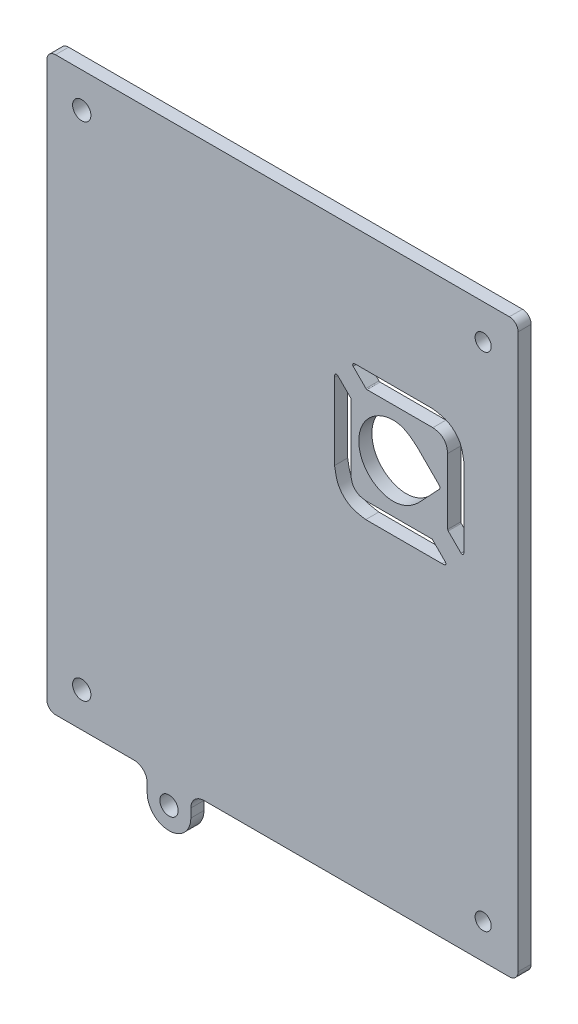
SolidWorks part; units mm, degrees
material "6061-T6 Black anodised"
ref_plane "Front Plane" through (0, 0, 0) normal (0, 0, 1) x (1, 0, 0)
ref_plane "Top Plane" through (0, 0, 0) normal (0, 1, 0) x (1, 0, 0)
ref_plane "Right Plane" through (0, 0, 0) normal (1, 0, 0) x (0, 0, -1)
sketch "Model" plane through (0, 0, 0) normal (0, 0, 1) x (1, 0, 0)
  line L0 (104.1673, 32.1811) -> (4.1672, 32.1811)
  line L1 (104.1673, 155.1806) -> (104.1673, 32.1811)
  line L2 (4.1672, 155.1806) -> (104.1673, 155.1806)
  line L3 (4.1672, 32.1811) -> (4.1672, 155.1806)
  line L4 (44.9158, 146.4259) -> (47.4224, 146.4259)
  line L5 (47.4224, 146.4259) -> (47.4224, 148.9326)
  line L6 (47.4224, 148.9326) -> (44.9158, 148.9326)
  line L7 (44.9158, 148.9326) -> (44.9158, 146.4259)
  line L8 (77.4127, 147.4278) -> (79.9193, 147.4278)
  line L9 (79.9193, 147.4278) -> (79.9193, 149.9344)
  line L10 (79.9193, 149.9344) -> (77.4127, 149.9344)
  line L11 (77.4127, 149.9344) -> (77.4127, 147.4278)
  line L12 (6.3266, 141.9721) -> (8.3592, 141.9721)
  line L13 (8.3592, 141.9721) -> (8.3592, 144.0047)
  line L14 (8.3592, 144.0047) -> (6.3266, 144.0047)
  line L15 (6.3266, 144.0047) -> (6.3266, 141.9721)
  line L16 (6.3266, 121.6529) -> (8.3592, 121.6529)
  line L17 (8.3592, 121.6529) -> (8.3592, 123.6855)
  line L18 (8.3592, 123.6855) -> (6.3266, 123.6855)
  line L19 (6.3266, 123.6855) -> (6.3266, 121.6529)
  line L20 (6.3266, 101.3324) -> (8.3592, 101.3324)
  line L21 (8.3592, 101.3324) -> (8.3592, 103.365)
  line L22 (8.3592, 103.365) -> (6.3266, 103.365)
  line L23 (6.3266, 103.365) -> (6.3266, 101.3324)
  line L24 (6.3266, 81.0118) -> (8.3592, 81.0118)
  line L25 (8.3592, 81.0118) -> (8.3592, 83.0444)
  line L26 (8.3592, 83.0444) -> (6.3266, 83.0444)
  line L27 (6.3266, 83.0444) -> (6.3266, 81.0118)
  line L28 (6.3266, 60.6927) -> (8.3592, 60.6927)
  line L29 (8.3592, 60.6927) -> (8.3592, 62.7253)
  line L30 (8.3592, 62.7253) -> (6.3266, 62.7253)
  line L31 (6.3266, 62.7253) -> (6.3266, 60.6927)
  line L32 (85.9221, 148.4144) -> (87.9547, 148.4144)
  line L33 (87.9547, 148.4144) -> (87.9547, 150.447)
  line L34 (87.9547, 150.447) -> (85.9221, 150.447)
  line L35 (85.9221, 150.447) -> (85.9221, 148.4144)
  line L36 (6.3266, 50.5324) -> (8.3592, 50.5324)
  line L37 (8.3592, 50.5324) -> (8.3592, 52.565)
  line L38 (8.3592, 52.565) -> (6.3266, 52.565)
  line L39 (6.3266, 52.565) -> (6.3266, 50.5324)
  line L40 (6.3266, 42.9118) -> (8.3592, 42.9118)
  line L41 (8.3592, 42.9118) -> (8.3592, 44.9444)
  line L42 (8.3592, 44.9444) -> (6.3266, 44.9444)
  line L43 (6.3266, 44.9444) -> (6.3266, 42.9118)
  line L44 (52.8726, 50.0418) -> (54.3815, 50.0418)
  line L45 (54.3815, 50.0418) -> (54.3815, 51.5508)
  line L46 (54.3815, 51.5508) -> (52.8726, 51.5508)
  line L47 (52.8726, 51.5508) -> (52.8726, 50.0418)
  line L48 (58.4219, 130.1637) -> (60.4545, 130.1637)
  line L49 (60.4545, 130.1637) -> (60.4545, 132.1963)
  line L50 (60.4545, 132.1963) -> (58.4219, 132.1963)
  line L51 (58.4219, 132.1963) -> (58.4219, 130.1637)
  line L52 (97.8807, 141.1439) -> (99.9133, 141.1439)
  line L53 (99.9133, 141.1439) -> (99.9133, 143.1765)
  line L54 (99.9133, 143.1765) -> (97.8807, 143.1765)
  line L55 (97.8807, 143.1765) -> (97.8807, 141.1439)
  line L56 (48.438, 37.3046) -> (48.438, 37.0552)
  line L57 (49.9456, 37.0552) -> (49.9456, 37.3046)
  line L58 (52.8877, 37.3046) -> (52.8877, 37.0552)
  line L59 (54.3967, 37.0552) -> (54.3967, 37.3046)
  line L60 (54.3126, 34.0993) -> (54.3126, 33.8995)
  line L61 (56.7201, 33.8995) -> (56.7201, 34.0993)
  line L62 (46.1133, 34.0993) -> (46.1133, 33.8995)
  line L63 (48.5207, 33.8995) -> (48.5207, 34.0993)
  line L64 (82.9607, 49.0165) -> (84.9933, 49.0165)
  line L65 (84.9933, 49.0165) -> (84.9933, 51.0492)
  line L66 (84.9933, 51.0492) -> (82.9607, 51.0492)
  line L67 (82.9607, 51.0492) -> (82.9607, 49.0165)
  line L68 (29.8828, 70.9163) -> (31.9154, 70.9163)
  line L69 (31.9154, 70.9163) -> (31.9154, 72.9489)
  line L70 (31.9154, 72.9489) -> (29.8828, 72.9489)
  line L71 (29.8828, 72.9489) -> (29.8828, 70.9163)
  line L72 (29.8828, 68.1658) -> (31.9154, 68.1658)
  line L73 (31.9154, 68.1658) -> (31.9154, 70.1984)
  line L74 (31.9154, 70.1984) -> (29.8828, 70.1984)
  line L75 (29.8828, 70.1984) -> (29.8828, 68.1658)
  line L76 (29.8828, 108.6649) -> (31.9154, 108.6649)
  line L77 (31.9154, 108.6649) -> (31.9154, 110.6975)
  line L78 (31.9154, 110.6975) -> (29.8828, 110.6975)
  line L79 (29.8828, 110.6975) -> (29.8828, 108.6649)
  line L80 (29.8828, 111.4141) -> (31.9154, 111.4141)
  line L81 (31.9154, 111.4141) -> (31.9154, 113.4467)
  line L82 (31.9154, 113.4467) -> (29.8828, 113.4467)
  line L83 (29.8828, 113.4467) -> (29.8828, 111.4141)
  line L84 (29.8828, 91.1652) -> (31.9154, 91.1652)
  line L85 (31.9154, 91.1652) -> (31.9154, 93.1978)
  line L86 (31.9154, 93.1978) -> (29.8828, 93.1978)
  line L87 (29.8828, 93.1978) -> (29.8828, 91.1652)
  line L88 (29.8828, 88.4147) -> (31.9154, 88.4147)
  line L89 (31.9154, 88.4147) -> (31.9154, 90.4473)
  line L90 (31.9154, 90.4473) -> (29.8828, 90.4473)
  line L91 (29.8828, 90.4473) -> (29.8828, 88.4147)
  line L92 (29.8828, 128.6658) -> (31.9154, 128.6658)
  line L93 (31.9154, 128.6658) -> (31.9154, 130.6984)
  line L94 (31.9154, 130.6984) -> (29.8828, 130.6984)
  line L95 (29.8828, 130.6984) -> (29.8828, 128.6658)
  line L96 (29.8828, 131.4163) -> (31.9154, 131.4163)
  line L97 (31.9154, 131.4163) -> (31.9154, 133.4489)
  line L98 (31.9154, 133.4489) -> (29.8828, 133.4489)
  line L99 (29.8828, 133.4489) -> (29.8828, 131.4163)
  line L100 (48.1611, 135.1453) -> (50.1937, 135.1453)
  line L101 (50.1937, 135.1453) -> (50.1937, 137.1779)
  line L102 (50.1937, 137.1779) -> (48.1611, 137.1779)
  line L103 (48.1611, 137.1779) -> (48.1611, 135.1453)
  line L104 (11.4074, 121.6529) -> (13.44, 121.6529)
  line L105 (13.44, 121.6529) -> (13.44, 123.6855)
  line L106 (13.44, 123.6855) -> (11.4074, 123.6855)
  line L107 (11.4074, 123.6855) -> (11.4074, 121.6529)
  line L108 (104.1673, 32.1811) -> (4.1672, 32.1811)
  line L109 (104.1673, 155.1806) -> (104.1673, 32.1811)
  line L110 (4.1672, 155.1806) -> (104.1673, 155.1806)
  line L111 (4.1672, 32.1811) -> (4.1672, 155.1806)
  spline S0 degree 3 poles (55.1711, 147.6799) (55.1711, 149.685) (52.1643, 149.685) (52.1643, 147.6799) knots 0 0 0 0 1 1 1 1
  spline S1 degree 3 poles (52.1643, 147.6799) (52.1643, 145.6749) (55.1711, 145.6749) (55.1711, 147.6799) knots 0 0 0 0 1 1 1 1
  spline S2 degree 3 poles (75.1706, 148.6804) (75.1706, 150.6854) (72.1637, 150.6854) (72.1637, 148.6804) knots 0 0 0 0 1 1 1 1
  spline S3 degree 3 poles (72.1637, 148.6804) (72.1637, 146.6754) (75.1706, 146.6754) (75.1706, 148.6804) knots 0 0 0 0 1 1 1 1
  spline S4 degree 3 poles (8.3592, 140.448) (8.3592, 141.8026) (6.3266, 141.8026) (6.3266, 140.448) knots 0 0 0 0 1 1 1 1
  spline S5 degree 3 poles (6.3266, 140.448) (6.3266, 139.0934) (8.3592, 139.0934) (8.3592, 140.448) knots 0 0 0 0 1 1 1 1
  spline S6 degree 3 poles (8.3592, 137.9083) (8.3592, 139.2629) (6.3266, 139.2629) (6.3266, 137.9083) knots 0 0 0 0 1 1 1 1
  spline S7 degree 3 poles (6.3266, 137.9083) (6.3266, 136.5537) (8.3592, 136.5537) (8.3592, 137.9083) knots 0 0 0 0 1 1 1 1
  spline S8 degree 3 poles (8.3592, 135.3686) (8.3592, 136.7232) (6.3266, 136.7232) (6.3266, 135.3686) knots 0 0 0 0 1 1 1 1
  spline S9 degree 3 poles (6.3266, 135.3686) (6.3266, 134.0139) (8.3592, 134.0139) (8.3592, 135.3686) knots 0 0 0 0 1 1 1 1
  spline S10 degree 3 poles (8.3592, 132.8288) (8.3592, 134.1834) (6.3266, 134.1834) (6.3266, 132.8288) knots 0 0 0 0 1 1 1 1
  spline S11 degree 3 poles (6.3266, 132.8288) (6.3266, 131.4742) (8.3592, 131.4742) (8.3592, 132.8288) knots 0 0 0 0 1 1 1 1
  spline S12 degree 3 poles (8.3592, 130.2891) (8.3592, 131.6437) (6.3266, 131.6437) (6.3266, 130.2891) knots 0 0 0 0 1 1 1 1
  spline S13 degree 3 poles (6.3266, 130.2891) (6.3266, 128.9331) (8.3592, 128.9331) (8.3592, 130.2891) knots 0 0 0 0 1 1 1 1
  spline S14 degree 3 poles (8.3592, 127.748) (8.3592, 129.1026) (6.3266, 129.1026) (6.3266, 127.748) knots 0 0 0 0 1 1 1 1
  spline S15 degree 3 poles (6.3266, 127.748) (6.3266, 126.3934) (8.3592, 126.3934) (8.3592, 127.748) knots 0 0 0 0 1 1 1 1
  spline S16 degree 3 poles (8.3592, 120.1288) (8.3592, 121.4834) (6.3266, 121.4834) (6.3266, 120.1288) knots 0 0 0 0 1 1 1 1
  spline S17 degree 3 poles (6.3266, 120.1288) (6.3266, 118.7742) (8.3592, 118.7742) (8.3592, 120.1288) knots 0 0 0 0 1 1 1 1
  spline S18 degree 3 poles (8.3592, 117.5891) (8.3592, 118.9437) (6.3266, 118.9437) (6.3266, 117.5891) knots 0 0 0 0 1 1 1 1
  spline S19 degree 3 poles (6.3266, 117.5891) (6.3266, 116.2331) (8.3592, 116.2331) (8.3592, 117.5891) knots 0 0 0 0 1 1 1 1
  spline S20 degree 3 poles (8.3592, 115.048) (8.3592, 116.4026) (6.3266, 116.4026) (6.3266, 115.048) knots 0 0 0 0 1 1 1 1
  spline S21 degree 3 poles (6.3266, 115.048) (6.3266, 113.6934) (8.3592, 113.6934) (8.3592, 115.048) knots 0 0 0 0 1 1 1 1
  spline S22 degree 3 poles (8.3592, 112.5083) (8.3592, 113.8629) (6.3266, 113.8629) (6.3266, 112.5083) knots 0 0 0 0 1 1 1 1
  spline S23 degree 3 poles (6.3266, 112.5083) (6.3266, 111.1537) (8.3592, 111.1537) (8.3592, 112.5083) knots 0 0 0 0 1 1 1 1
  spline S24 degree 3 poles (8.3592, 109.9686) (8.3592, 111.3232) (6.3266, 111.3232) (6.3266, 109.9686) knots 0 0 0 0 1 1 1 1
  spline S25 degree 3 poles (6.3266, 109.9686) (6.3266, 108.6139) (8.3592, 108.6139) (8.3592, 109.9686) knots 0 0 0 0 1 1 1 1
  spline S26 degree 3 poles (8.3592, 107.4288) (8.3592, 108.7834) (6.3266, 108.7834) (6.3266, 107.4288) knots 0 0 0 0 1 1 1 1
  spline S27 degree 3 poles (6.3266, 107.4288) (6.3266, 106.0742) (8.3592, 106.0742) (8.3592, 107.4288) knots 0 0 0 0 1 1 1 1
  spline S28 degree 3 poles (8.3592, 99.8083) (8.3592, 101.1629) (6.3266, 101.1629) (6.3266, 99.8083) knots 0 0 0 0 1 1 1 1
  spline S29 degree 3 poles (6.3266, 99.8083) (6.3266, 98.4537) (8.3592, 98.4537) (8.3592, 99.8083) knots 0 0 0 0 1 1 1 1
  spline S30 degree 3 poles (8.3592, 97.2686) (8.3592, 98.6232) (6.3266, 98.6232) (6.3266, 97.2686) knots 0 0 0 0 1 1 1 1
  spline S31 degree 3 poles (6.3266, 97.2686) (6.3266, 95.9139) (8.3592, 95.9139) (8.3592, 97.2686) knots 0 0 0 0 1 1 1 1
  spline S32 degree 3 poles (8.3592, 94.7288) (8.3592, 96.0834) (6.3266, 96.0834) (6.3266, 94.7288) knots 0 0 0 0 1 1 1 1
  spline S33 degree 3 poles (6.3266, 94.7288) (6.3266, 93.3742) (8.3592, 93.3742) (8.3592, 94.7288) knots 0 0 0 0 1 1 1 1
  spline S34 degree 3 poles (8.3592, 92.1891) (8.3592, 93.5437) (6.3266, 93.5437) (6.3266, 92.1891) knots 0 0 0 0 1 1 1 1
  spline S35 degree 3 poles (6.3266, 92.1891) (6.3266, 90.8331) (8.3592, 90.8331) (8.3592, 92.1891) knots 0 0 0 0 1 1 1 1
  spline S36 degree 3 poles (8.3592, 89.648) (8.3592, 91.0026) (6.3266, 91.0026) (6.3266, 89.648) knots 0 0 0 0 1 1 1 1
  spline S37 degree 3 poles (6.3266, 89.648) (6.3266, 88.2934) (8.3592, 88.2934) (8.3592, 89.648) knots 0 0 0 0 1 1 1 1
  spline S38 degree 3 poles (8.3592, 87.1083) (8.3592, 88.4629) (6.3266, 88.4629) (6.3266, 87.1083) knots 0 0 0 0 1 1 1 1
  spline S39 degree 3 poles (6.3266, 87.1083) (6.3266, 85.7537) (8.3592, 85.7537) (8.3592, 87.1083) knots 0 0 0 0 1 1 1 1
  spline S40 degree 3 poles (8.3592, 79.4891) (8.3592, 80.8437) (6.3266, 80.8437) (6.3266, 79.4891) knots 0 0 0 0 1 1 1 1
  spline S41 degree 3 poles (6.3266, 79.4891) (6.3266, 78.1331) (8.3592, 78.1331) (8.3592, 79.4891) knots 0 0 0 0 1 1 1 1
  spline S42 degree 3 poles (8.3592, 76.948) (8.3592, 78.3026) (6.3266, 78.3026) (6.3266, 76.948) knots 0 0 0 0 1 1 1 1
  spline S43 degree 3 poles (6.3266, 76.948) (6.3266, 75.5934) (8.3592, 75.5934) (8.3592, 76.948) knots 0 0 0 0 1 1 1 1
  spline S44 degree 3 poles (8.3592, 74.4083) (8.3592, 75.7629) (6.3266, 75.7629) (6.3266, 74.4083) knots 0 0 0 0 1 1 1 1
  spline S45 degree 3 poles (6.3266, 74.4083) (6.3266, 73.0537) (8.3592, 73.0537) (8.3592, 74.4083) knots 0 0 0 0 1 1 1 1
  spline S46 degree 3 poles (8.3592, 71.8685) (8.3592, 73.2232) (6.3266, 73.2232) (6.3266, 71.8685) knots 0 0 0 0 1 1 1 1
  spline S47 degree 3 poles (6.3266, 71.8685) (6.3266, 70.5139) (8.3592, 70.5139) (8.3592, 71.8685) knots 0 0 0 0 1 1 1 1
  spline S48 degree 3 poles (8.3592, 69.3288) (8.3592, 70.6834) (6.3266, 70.6834) (6.3266, 69.3288) knots 0 0 0 0 1 1 1 1
  spline S49 degree 3 poles (6.3266, 69.3288) (6.3266, 67.9742) (8.3592, 67.9742) (8.3592, 69.3288) knots 0 0 0 0 1 1 1 1
  spline S50 degree 3 poles (8.3592, 66.7891) (8.3592, 68.1437) (6.3266, 68.1437) (6.3266, 66.7891) knots 0 0 0 0 1 1 1 1
  spline S51 degree 3 poles (6.3266, 66.7891) (6.3266, 65.4331) (8.3592, 65.4331) (8.3592, 66.7891) knots 0 0 0 0 1 1 1 1
  spline S52 degree 3 poles (8.3592, 59.1686) (8.3592, 60.5232) (6.3266, 60.5232) (6.3266, 59.1686) knots 0 0 0 0 1 1 1 1
  spline S53 degree 3 poles (6.3266, 59.1686) (6.3266, 57.8139) (8.3592, 57.8139) (8.3592, 59.1686) knots 0 0 0 0 1 1 1 1
  spline S54 degree 3 poles (8.3592, 56.6288) (8.3592, 57.9834) (6.3266, 57.9834) (6.3266, 56.6288) knots 0 0 0 0 1 1 1 1
  spline S55 degree 3 poles (6.3266, 56.6288) (6.3266, 55.2742) (8.3592, 55.2742) (8.3592, 56.6288) knots 0 0 0 0 1 1 1 1
  spline S56 degree 3 poles (8.3592, 54.0891) (8.3592, 55.4437) (6.3266, 55.4437) (6.3266, 54.0891) knots 0 0 0 0 1 1 1 1
  spline S57 degree 3 poles (6.3266, 54.0891) (6.3266, 52.7331) (8.3592, 52.7331) (8.3592, 54.0891) knots 0 0 0 0 1 1 1 1
  spline S58 degree 3 poles (85.4149, 149.4301) (85.4149, 150.7847) (83.3823, 150.7847) (83.3823, 149.4301) knots 0 0 0 0 1 1 1 1
  spline S59 degree 3 poles (83.3823, 149.4301) (83.3823, 148.0754) (85.4149, 148.0754) (85.4149, 149.4301) knots 0 0 0 0 1 1 1 1
  spline S60 degree 3 poles (8.3592, 49.0083) (8.3592, 50.3629) (6.3266, 50.3629) (6.3266, 49.0083) knots 0 0 0 0 1 1 1 1
  spline S61 degree 3 poles (6.3266, 49.0083) (6.3266, 47.6537) (8.3592, 47.6537) (8.3592, 49.0083) knots 0 0 0 0 1 1 1 1
  spline S62 degree 3 poles (8.3592, 41.3891) (8.3592, 42.7437) (6.3266, 42.7437) (6.3266, 41.3891) knots 0 0 0 0 1 1 1 1
  spline S63 degree 3 poles (6.3266, 41.3891) (6.3266, 40.0331) (8.3592, 40.0331) (8.3592, 41.3891) knots 0 0 0 0 1 1 1 1
  spline S64 degree 3 poles (54.3815, 52.0661) (54.3815, 53.0721) (52.8726, 53.0721) (52.8726, 52.0661) knots 0 0 0 0 1 1 1 1
  spline S65 degree 3 poles (52.8726, 52.0661) (52.8726, 51.0602) (54.3815, 51.0602) (54.3815, 52.0661) knots 0 0 0 0 1 1 1 1
  spline S66 degree 3 poles (55.6507, 50.797) (55.6507, 51.8029) (54.1417, 51.8029) (54.1417, 50.797) knots 0 0 0 0 1 1 1 1
  spline S67 degree 3 poles (54.1417, 50.797) (54.1417, 49.791) (55.6507, 49.791) (55.6507, 50.797) knots 0 0 0 0 1 1 1 1
  spline S68 degree 3 poles (55.6507, 52.0661) (55.6507, 53.0721) (54.1417, 53.0721) (54.1417, 52.0661) knots 0 0 0 0 1 1 1 1
  spline S69 degree 3 poles (54.1417, 52.0661) (54.1417, 51.0602) (55.6507, 51.0602) (55.6507, 52.0661) knots 0 0 0 0 1 1 1 1
  spline S70 degree 3 poles (56.9212, 50.797) (56.9212, 51.8029) (55.4123, 51.8029) (55.4123, 50.797) knots 0 0 0 0 1 1 1 1
  spline S71 degree 3 poles (55.4123, 50.797) (55.4123, 49.791) (56.9212, 49.791) (56.9212, 50.797) knots 0 0 0 0 1 1 1 1
  spline S72 degree 3 poles (56.9212, 52.0661) (56.9212, 53.0721) (55.4123, 53.0721) (55.4123, 52.0661) knots 0 0 0 0 1 1 1 1
  spline S73 degree 3 poles (55.4123, 52.0661) (55.4123, 51.0602) (56.9212, 51.0602) (56.9212, 52.0661) knots 0 0 0 0 1 1 1 1
  spline S74 degree 3 poles (58.1904, 50.797) (58.1904, 51.8029) (56.6828, 51.8029) (56.6828, 50.797) knots 0 0 0 0 1 1 1 1
  spline S75 degree 3 poles (56.6828, 50.797) (56.6828, 49.791) (58.1904, 49.791) (58.1904, 50.797) knots 0 0 0 0 1 1 1 1
  spline S76 degree 3 poles (58.1904, 52.0661) (58.1904, 53.0721) (56.6828, 53.0721) (56.6828, 52.0661) knots 0 0 0 0 1 1 1 1
  spline S77 degree 3 poles (56.6828, 52.0661) (56.6828, 51.0602) (58.1904, 51.0602) (58.1904, 52.0661) knots 0 0 0 0 1 1 1 1
  spline S78 degree 3 poles (59.461, 50.797) (59.461, 51.8029) (57.952, 51.8029) (57.952, 50.797) knots 0 0 0 0 1 1 1 1
  spline S79 degree 3 poles (57.952, 50.797) (57.952, 49.791) (59.461, 49.791) (59.461, 50.797) knots 0 0 0 0 1 1 1 1
  spline S80 degree 3 poles (59.461, 52.0661) (59.461, 53.0721) (57.952, 53.0721) (57.952, 52.0661) knots 0 0 0 0 1 1 1 1
  spline S81 degree 3 poles (57.952, 52.0661) (57.952, 51.0602) (59.461, 51.0602) (59.461, 52.0661) knots 0 0 0 0 1 1 1 1
  spline S82 degree 3 poles (57.9148, 131.1793) (57.9148, 132.5353) (55.8822, 132.5353) (55.8822, 131.1793) knots 0 0 0 0 1 1 1 1
  spline S83 degree 3 poles (55.8822, 131.1793) (55.8822, 129.8247) (57.9148, 129.8247) (57.9148, 131.1793) knots 0 0 0 0 1 1 1 1
  spline S84 degree 3 poles (63.2437, 36.9311) (63.2437, 37.9371) (61.7347, 37.9371) (61.7347, 36.9311) knots 0 0 0 0 1 1 1 1
  spline S85 degree 3 poles (61.7347, 36.9311) (61.7347, 35.9252) (63.2437, 35.9252) (63.2437, 36.9311) knots 0 0 0 0 1 1 1 1
  spline S86 degree 3 poles (71.2239, 36.9311) (71.2239, 37.9371) (69.715, 37.9371) (69.715, 36.9311) knots 0 0 0 0 1 1 1 1
  spline S87 degree 3 poles (69.715, 36.9311) (69.715, 35.9252) (71.2239, 35.9252) (71.2239, 36.9311) knots 0 0 0 0 1 1 1 1
  spline S88 degree 3 poles (102.453, 142.1609) (102.453, 143.5155) (100.4204, 143.5155) (100.4204, 142.1609) knots 0 0 0 0 1 1 1 1
  spline S89 degree 3 poles (100.4204, 142.1609) (100.4204, 140.8063) (102.453, 140.8063) (102.453, 142.1609) knots 0 0 0 0 1 1 1 1
  spline S90 degree 3 poles (99.9133, 129.4609) (99.9133, 130.8155) (97.8807, 130.8155) (97.8807, 129.4609) knots 0 0 0 0 1 1 1 1
  spline S91 degree 3 poles (97.8807, 129.4609) (97.8807, 128.1063) (99.9133, 128.1063) (99.9133, 129.4609) knots 0 0 0 0 1 1 1 1
  spline S92 degree 3 poles (102.453, 139.6198) (102.453, 140.9744) (100.4204, 140.9744) (100.4204, 139.6198) knots 0 0 0 0 1 1 1 1
  spline S93 degree 3 poles (100.4204, 139.6198) (100.4204, 138.2652) (102.453, 138.2652) (102.453, 139.6198) knots 0 0 0 0 1 1 1 1
  spline S94 degree 3 poles (99.9133, 126.9198) (99.9133, 128.2744) (97.8807, 128.2744) (97.8807, 126.9198) knots 0 0 0 0 1 1 1 1
  spline S95 degree 3 poles (97.8807, 126.9198) (97.8807, 125.5652) (99.9133, 125.5652) (99.9133, 126.9198) knots 0 0 0 0 1 1 1 1
  spline S96 degree 3 poles (102.453, 137.0801) (102.453, 138.4347) (100.4204, 138.4347) (100.4204, 137.0801) knots 0 0 0 0 1 1 1 1
  spline S97 degree 3 poles (100.4204, 137.0801) (100.4204, 135.7255) (102.453, 135.7255) (102.453, 137.0801) knots 0 0 0 0 1 1 1 1
  spline S98 degree 3 poles (99.9133, 124.3801) (99.9133, 125.7347) (97.8807, 125.7347) (97.8807, 124.3801) knots 0 0 0 0 1 1 1 1
  spline S99 degree 3 poles (97.8807, 124.3801) (97.8807, 123.0255) (99.9133, 123.0255) (99.9133, 124.3801) knots 0 0 0 0 1 1 1 1
  spline S100 degree 3 poles (102.453, 134.5403) (102.453, 135.895) (100.4204, 135.895) (100.4204, 134.5403) knots 0 0 0 0 1 1 1 1
  spline S101 degree 3 poles (100.4204, 134.5403) (100.4204, 133.1857) (102.453, 133.1857) (102.453, 134.5403) knots 0 0 0 0 1 1 1 1
  spline S102 degree 3 poles (99.9133, 121.8404) (99.9133, 123.195) (97.8807, 123.195) (97.8807, 121.8404) knots 0 0 0 0 1 1 1 1
  spline S103 degree 3 poles (97.8807, 121.8404) (97.8807, 120.4857) (99.9133, 120.4857) (99.9133, 121.8404) knots 0 0 0 0 1 1 1 1
  spline S104 degree 3 poles (102.453, 132.0006) (102.453, 133.3552) (100.4204, 133.3552) (100.4204, 132.0006) knots 0 0 0 0 1 1 1 1
  spline S105 degree 3 poles (100.4204, 132.0006) (100.4204, 130.646) (102.453, 130.646) (102.453, 132.0006) knots 0 0 0 0 1 1 1 1
  spline S106 degree 3 poles (99.9133, 119.3006) (99.9133, 120.6552) (97.8807, 120.6552) (97.8807, 119.3006) knots 0 0 0 0 1 1 1 1
  spline S107 degree 3 poles (97.8807, 119.3006) (97.8807, 117.946) (99.9133, 117.946) (99.9133, 119.3006) knots 0 0 0 0 1 1 1 1
  spline S108 degree 3 poles (102.453, 129.4609) (102.453, 130.8155) (100.4204, 130.8155) (100.4204, 129.4609) knots 0 0 0 0 1 1 1 1
  spline S109 degree 3 poles (100.4204, 129.4609) (100.4204, 128.1063) (102.453, 128.1063) (102.453, 129.4609) knots 0 0 0 0 1 1 1 1
  spline S110 degree 3 poles (99.9133, 116.7609) (99.9133, 118.1155) (97.8807, 118.1155) (97.8807, 116.7609) knots 0 0 0 0 1 1 1 1
  spline S111 degree 3 poles (97.8807, 116.7609) (97.8807, 115.4063) (99.9133, 115.4063) (99.9133, 116.7609) knots 0 0 0 0 1 1 1 1
  spline S112 degree 3 poles (102.453, 126.9198) (102.453, 128.2744) (100.4204, 128.2744) (100.4204, 126.9198) knots 0 0 0 0 1 1 1 1
  spline S113 degree 3 poles (100.4204, 126.9198) (100.4204, 125.5652) (102.453, 125.5652) (102.453, 126.9198) knots 0 0 0 0 1 1 1 1
  spline S114 degree 3 poles (99.9133, 114.2198) (99.9133, 115.5744) (97.8807, 115.5744) (97.8807, 114.2198) knots 0 0 0 0 1 1 1 1
  spline S115 degree 3 poles (97.8807, 114.2198) (97.8807, 112.8652) (99.9133, 112.8652) (99.9133, 114.2198) knots 0 0 0 0 1 1 1 1
  spline S116 degree 3 poles (102.453, 124.3801) (102.453, 125.7347) (100.4204, 125.7347) (100.4204, 124.3801) knots 0 0 0 0 1 1 1 1
  spline S117 degree 3 poles (100.4204, 124.3801) (100.4204, 123.0255) (102.453, 123.0255) (102.453, 124.3801) knots 0 0 0 0 1 1 1 1
  spline S118 degree 3 poles (99.9133, 111.6801) (99.9133, 113.0347) (97.8807, 113.0347) (97.8807, 111.6801) knots 0 0 0 0 1 1 1 1
  spline S119 degree 3 poles (97.8807, 111.6801) (97.8807, 110.3255) (99.9133, 110.3255) (99.9133, 111.6801) knots 0 0 0 0 1 1 1 1
  spline S120 degree 3 poles (102.453, 121.8404) (102.453, 123.195) (100.4204, 123.195) (100.4204, 121.8404) knots 0 0 0 0 1 1 1 1
  spline S121 degree 3 poles (100.4204, 121.8404) (100.4204, 120.4857) (102.453, 120.4857) (102.453, 121.8404) knots 0 0 0 0 1 1 1 1
  spline S122 degree 3 poles (99.9133, 109.1404) (99.9133, 110.495) (97.8807, 110.495) (97.8807, 109.1404) knots 0 0 0 0 1 1 1 1
  spline S123 degree 3 poles (97.8807, 109.1404) (97.8807, 107.7857) (99.9133, 107.7857) (99.9133, 109.1404) knots 0 0 0 0 1 1 1 1
  spline S124 degree 3 poles (102.453, 119.3006) (102.453, 120.6552) (100.4204, 120.6552) (100.4204, 119.3006) knots 0 0 0 0 1 1 1 1
  spline S125 degree 3 poles (100.4204, 119.3006) (100.4204, 117.946) (102.453, 117.946) (102.453, 119.3006) knots 0 0 0 0 1 1 1 1
  spline S126 degree 3 poles (99.9133, 106.6006) (99.9133, 107.9552) (97.8807, 107.9552) (97.8807, 106.6006) knots 0 0 0 0 1 1 1 1
  spline S127 degree 3 poles (97.8807, 106.6006) (97.8807, 105.246) (99.9133, 105.246) (99.9133, 106.6006) knots 0 0 0 0 1 1 1 1
  spline S128 degree 3 poles (102.453, 116.7609) (102.453, 118.1155) (100.4204, 118.1155) (100.4204, 116.7609) knots 0 0 0 0 1 1 1 1
  spline S129 degree 3 poles (100.4204, 116.7609) (100.4204, 115.4063) (102.453, 115.4063) (102.453, 116.7609) knots 0 0 0 0 1 1 1 1
  spline S130 degree 3 poles (99.9133, 104.0609) (99.9133, 105.4155) (97.8807, 105.4155) (97.8807, 104.0609) knots 0 0 0 0 1 1 1 1
  spline S131 degree 3 poles (97.8807, 104.0609) (97.8807, 102.7063) (99.9133, 102.7063) (99.9133, 104.0609) knots 0 0 0 0 1 1 1 1
  spline S132 degree 3 poles (102.453, 114.2198) (102.453, 115.5744) (100.4204, 115.5744) (100.4204, 114.2198) knots 0 0 0 0 1 1 1 1
  spline S133 degree 3 poles (100.4204, 114.2198) (100.4204, 112.8652) (102.453, 112.8652) (102.453, 114.2198) knots 0 0 0 0 1 1 1 1
  spline S134 degree 3 poles (102.453, 111.6801) (102.453, 113.0347) (100.4204, 113.0347) (100.4204, 111.6801) knots 0 0 0 0 1 1 1 1
  spline S135 degree 3 poles (100.4204, 111.6801) (100.4204, 110.3255) (102.453, 110.3255) (102.453, 111.6801) knots 0 0 0 0 1 1 1 1
  spline S136 degree 3 poles (99.9133, 101.5198) (99.9133, 102.8744) (97.8807, 102.8744) (97.8807, 101.5198) knots 0 0 0 0 1 1 1 1
  spline S137 degree 3 poles (97.8807, 101.5198) (97.8807, 100.1652) (99.9133, 100.1652) (99.9133, 101.5198) knots 0 0 0 0 1 1 1 1
  spline S138 degree 3 poles (102.453, 109.1404) (102.453, 110.495) (100.4204, 110.495) (100.4204, 109.1404) knots 0 0 0 0 1 1 1 1
  spline S139 degree 3 poles (100.4204, 109.1404) (100.4204, 107.7857) (102.453, 107.7857) (102.453, 109.1404) knots 0 0 0 0 1 1 1 1
  spline S140 degree 3 poles (102.453, 104.0609) (102.453, 105.4155) (100.4204, 105.4155) (100.4204, 104.0609) knots 0 0 0 0 1 1 1 1
  spline S141 degree 3 poles (100.4204, 104.0609) (100.4204, 102.7063) (102.453, 102.7063) (102.453, 104.0609) knots 0 0 0 0 1 1 1 1
  spline S142 degree 3 poles (102.453, 101.5198) (102.453, 102.8744) (100.4204, 102.8744) (100.4204, 101.5198) knots 0 0 0 0 1 1 1 1
  spline S143 degree 3 poles (100.4204, 101.5198) (100.4204, 100.1652) (102.453, 100.1652) (102.453, 101.5198) knots 0 0 0 0 1 1 1 1
  spline S144 degree 3 poles (102.453, 98.9801) (102.453, 100.3347) (100.4204, 100.3347) (100.4204, 98.9801) knots 0 0 0 0 1 1 1 1
  spline S145 degree 3 poles (100.4204, 98.9801) (100.4204, 97.6255) (102.453, 97.6255) (102.453, 98.9801) knots 0 0 0 0 1 1 1 1
  spline S146 degree 3 poles (102.453, 96.4404) (102.453, 97.795) (100.4204, 97.795) (100.4204, 96.4404) knots 0 0 0 0 1 1 1 1
  spline S147 degree 3 poles (100.4204, 96.4404) (100.4204, 95.0857) (102.453, 95.0857) (102.453, 96.4404) knots 0 0 0 0 1 1 1 1
  spline S148 degree 3 poles (99.9133, 98.9801) (99.9133, 100.3347) (97.8807, 100.3347) (97.8807, 98.9801) knots 0 0 0 0 1 1 1 1
  spline S149 degree 3 poles (97.8807, 98.9801) (97.8807, 97.6255) (99.9133, 97.6255) (99.9133, 98.9801) knots 0 0 0 0 1 1 1 1
  spline S150 degree 3 poles (99.9133, 96.4404) (99.9133, 97.795) (97.8807, 97.795) (97.8807, 96.4404) knots 0 0 0 0 1 1 1 1
  spline S151 degree 3 poles (97.8807, 96.4404) (97.8807, 95.0857) (99.9133, 95.0857) (99.9133, 96.4404) knots 0 0 0 0 1 1 1 1
  spline S152 degree 3 poles (99.9133, 139.6198) (99.9133, 140.9744) (97.8807, 140.9744) (97.8807, 139.6198) knots 0 0 0 0 1 1 1 1
  spline S153 degree 3 poles (97.8807, 139.6198) (97.8807, 138.2652) (99.9133, 138.2652) (99.9133, 139.6198) knots 0 0 0 0 1 1 1 1
  spline S154 degree 3 poles (99.9133, 137.0801) (99.9133, 138.4347) (97.8807, 138.4347) (97.8807, 137.0801) knots 0 0 0 0 1 1 1 1
  spline S155 degree 3 poles (97.8807, 137.0801) (97.8807, 135.7255) (99.9133, 135.7255) (99.9133, 137.0801) knots 0 0 0 0 1 1 1 1
  spline S156 degree 3 poles (99.9133, 134.5403) (99.9133, 135.895) (97.8807, 135.895) (97.8807, 134.5403) knots 0 0 0 0 1 1 1 1
  spline S157 degree 3 poles (97.8807, 134.5403) (97.8807, 133.1857) (99.9133, 133.1857) (99.9133, 134.5403) knots 0 0 0 0 1 1 1 1
  spline S158 degree 3 poles (99.9133, 132.0006) (99.9133, 133.3552) (97.8807, 133.3552) (97.8807, 132.0006) knots 0 0 0 0 1 1 1 1
  spline S159 degree 3 poles (97.8807, 132.0006) (97.8807, 130.646) (99.9133, 130.646) (99.9133, 132.0006) knots 0 0 0 0 1 1 1 1
  spline S160 degree 3 poles (99.9133, 93.9006) (99.9133, 95.2552) (97.8807, 95.2552) (97.8807, 93.9006) knots 0 0 0 0 1 1 1 1
  spline S161 degree 3 poles (97.8807, 93.9006) (97.8807, 92.546) (99.9133, 92.546) (99.9133, 93.9006) knots 0 0 0 0 1 1 1 1
  spline S162 degree 3 poles (102.453, 93.9006) (102.453, 95.2552) (100.4204, 95.2552) (100.4204, 93.9006) knots 0 0 0 0 1 1 1 1
  spline S163 degree 3 poles (100.4204, 93.9006) (100.4204, 92.546) (102.453, 92.546) (102.453, 93.9006) knots 0 0 0 0 1 1 1 1
  spline S164 degree 3 poles (102.453, 106.6006) (102.453, 107.9552) (100.4204, 107.9552) (100.4204, 106.6006) knots 0 0 0 0 1 1 1 1
  spline S165 degree 3 poles (100.4204, 106.6006) (100.4204, 105.246) (102.453, 105.246) (102.453, 106.6006) knots 0 0 0 0 1 1 1 1
  spline S166 degree 3 poles (99.9133, 91.3609) (99.9133, 92.7155) (97.8807, 92.7155) (97.8807, 91.3609) knots 0 0 0 0 1 1 1 1
  spline S167 degree 3 poles (97.8807, 91.3609) (97.8807, 90.0063) (99.9133, 90.0063) (99.9133, 91.3609) knots 0 0 0 0 1 1 1 1
  spline S168 degree 3 poles (102.453, 91.3609) (102.453, 92.7155) (100.4204, 92.7155) (100.4204, 91.3609) knots 0 0 0 0 1 1 1 1
  spline S169 degree 3 poles (100.4204, 91.3609) (100.4204, 90.0063) (102.453, 90.0063) (102.453, 91.3609) knots 0 0 0 0 1 1 1 1
  spline S170 degree 3 poles (99.9133, 88.8198) (99.9133, 90.1744) (97.8807, 90.1744) (97.8807, 88.8198) knots 0 0 0 0 1 1 1 1
  spline S171 degree 3 poles (97.8807, 88.8198) (97.8807, 87.4652) (99.9133, 87.4652) (99.9133, 88.8198) knots 0 0 0 0 1 1 1 1
  spline S172 degree 3 poles (102.453, 88.8198) (102.453, 90.1744) (100.4204, 90.1744) (100.4204, 88.8198) knots 0 0 0 0 1 1 1 1
  spline S173 degree 3 poles (100.4204, 88.8198) (100.4204, 87.4652) (102.453, 87.4652) (102.453, 88.8198) knots 0 0 0 0 1 1 1 1
  spline S174 degree 3 poles (99.9133, 86.2801) (99.9133, 87.6347) (97.8807, 87.6347) (97.8807, 86.2801) knots 0 0 0 0 1 1 1 1
  spline S175 degree 3 poles (97.8807, 86.2801) (97.8807, 84.9255) (99.9133, 84.9255) (99.9133, 86.2801) knots 0 0 0 0 1 1 1 1
  spline S176 degree 3 poles (102.453, 86.2801) (102.453, 87.6347) (100.4204, 87.6347) (100.4204, 86.2801) knots 0 0 0 0 1 1 1 1
  spline S177 degree 3 poles (100.4204, 86.2801) (100.4204, 84.9255) (102.453, 84.9255) (102.453, 86.2801) knots 0 0 0 0 1 1 1 1
  spline S178 degree 3 poles (99.9133, 83.7404) (99.9133, 85.095) (97.8807, 85.095) (97.8807, 83.7404) knots 0 0 0 0 1 1 1 1
  spline S179 degree 3 poles (97.8807, 83.7404) (97.8807, 82.3857) (99.9133, 82.3857) (99.9133, 83.7404) knots 0 0 0 0 1 1 1 1
  spline S180 degree 3 poles (102.453, 83.7404) (102.453, 85.095) (100.4204, 85.095) (100.4204, 83.7404) knots 0 0 0 0 1 1 1 1
  spline S181 degree 3 poles (100.4204, 83.7404) (100.4204, 82.3857) (102.453, 82.3857) (102.453, 83.7404) knots 0 0 0 0 1 1 1 1
  spline S182 degree 3 poles (99.9133, 81.2006) (99.9133, 82.5552) (97.8807, 82.5552) (97.8807, 81.2006) knots 0 0 0 0 1 1 1 1
  spline S183 degree 3 poles (97.8807, 81.2006) (97.8807, 79.846) (99.9133, 79.846) (99.9133, 81.2006) knots 0 0 0 0 1 1 1 1
  spline S184 degree 3 poles (102.453, 81.2006) (102.453, 82.5552) (100.4204, 82.5552) (100.4204, 81.2006) knots 0 0 0 0 1 1 1 1
  spline S185 degree 3 poles (100.4204, 81.2006) (100.4204, 79.846) (102.453, 79.846) (102.453, 81.2006) knots 0 0 0 0 1 1 1 1
  spline S186 degree 3 poles (49.9456, 37.3046) (49.9456, 38.3106) (48.438, 38.3106) (48.438, 37.3046) knots 0 0 0 0 1 1 1 1
  spline S187 degree 3 poles (48.438, 37.0552) (48.438, 36.0492) (49.9456, 36.0492) (49.9456, 37.0552) knots 0 0 0 0 1 1 1 1
  spline S188 degree 3 poles (54.3967, 37.3046) (54.3967, 38.3106) (52.8877, 38.3106) (52.8877, 37.3046) knots 0 0 0 0 1 1 1 1
  spline S189 degree 3 poles (52.8877, 37.0552) (52.8877, 36.0492) (54.3967, 36.0492) (54.3967, 37.0552) knots 0 0 0 0 1 1 1 1
  spline S190 degree 3 poles (56.7201, 34.0993) (56.7201, 35.7047) (54.3126, 35.7047) (54.3126, 34.0993) knots 0 0 0 0 1 1 1 1
  spline S191 degree 3 poles (54.3126, 33.8995) (54.3126, 32.2941) (56.7201, 32.2941) (56.7201, 33.8995) knots 0 0 0 0 1 1 1 1
  spline S192 degree 3 poles (48.5207, 34.0993) (48.5207, 35.7047) (46.1133, 35.7047) (46.1133, 34.0993) knots 0 0 0 0 1 1 1 1
  spline S193 degree 3 poles (46.1133, 33.8995) (46.1133, 32.2941) (48.5207, 32.2941) (48.5207, 33.8995) knots 0 0 0 0 1 1 1 1
  spline S194 degree 3 poles (54.4711, 34.0001) (54.4711, 34.9054) (53.1123, 34.9054) (53.1123, 34.0001) knots 0 0 0 0 1 1 1 1
  spline S195 degree 3 poles (53.1123, 34.0001) (53.1123, 33.0933) (54.4711, 33.0933) (54.4711, 34.0001) knots 0 0 0 0 1 1 1 1
  spline S196 degree 3 poles (49.721, 34.0001) (49.721, 34.9054) (48.3623, 34.9054) (48.3623, 34.0001) knots 0 0 0 0 1 1 1 1
  spline S197 degree 3 poles (48.3623, 34.0001) (48.3623, 33.0933) (49.721, 33.0933) (49.721, 34.0001) knots 0 0 0 0 1 1 1 1
  spline S198 degree 3 poles (84.606, 43.6822) (84.606, 46.2205) (80.7985, 46.2205) (80.7985, 43.6822) knots 0 0 0 0 1 1 1 1
  spline S199 degree 3 poles (80.7985, 43.6822) (80.7985, 41.1438) (84.606, 41.1438) (84.606, 43.6822) knots 0 0 0 0 1 1 1 1
  spline S200 degree 3 poles (96.0355, 43.6822) (96.0355, 46.2205) (92.228, 46.2205) (92.228, 43.6822) knots 0 0 0 0 1 1 1 1
  spline S201 degree 3 poles (92.228, 43.6822) (92.228, 41.1438) (96.0355, 41.1438) (96.0355, 43.6822) knots 0 0 0 0 1 1 1 1
  spline S202 degree 3 poles (93.8775, 52.5719) (93.8775, 53.9265) (91.8462, 53.9265) (91.8462, 52.5719) knots 0 0 0 0 1 1 1 1
  spline S203 degree 3 poles (91.8462, 52.5719) (91.8462, 51.2173) (93.8775, 51.2173) (93.8775, 52.5719) knots 0 0 0 0 1 1 1 1
  spline S204 degree 3 poles (92.6124, 50.0322) (92.6124, 51.3868) (90.5812, 51.3868) (90.5812, 50.0322) knots 0 0 0 0 1 1 1 1
  spline S205 degree 3 poles (90.5812, 50.0322) (90.5812, 48.6775) (92.6124, 48.6775) (92.6124, 50.0322) knots 0 0 0 0 1 1 1 1
  spline S206 degree 3 poles (91.3377, 52.5719) (91.3377, 53.9265) (89.3065, 53.9265) (89.3065, 52.5719) knots 0 0 0 0 1 1 1 1
  spline S207 degree 3 poles (89.3065, 52.5719) (89.3065, 51.2173) (91.3377, 51.2173) (91.3377, 52.5719) knots 0 0 0 0 1 1 1 1
  spline S208 degree 3 poles (90.0727, 50.0322) (90.0727, 51.3868) (88.0415, 51.3868) (88.0415, 50.0322) knots 0 0 0 0 1 1 1 1
  spline S209 degree 3 poles (88.0415, 50.0322) (88.0415, 48.6775) (90.0727, 48.6775) (90.0727, 50.0322) knots 0 0 0 0 1 1 1 1
  spline S210 degree 3 poles (88.798, 52.5719) (88.798, 53.9265) (86.7654, 53.9265) (86.7654, 52.5719) knots 0 0 0 0 1 1 1 1
  spline S211 degree 3 poles (86.7654, 52.5719) (86.7654, 51.2173) (88.798, 51.2173) (88.798, 52.5719) knots 0 0 0 0 1 1 1 1
  spline S212 degree 3 poles (87.533, 50.0322) (87.533, 51.3868) (85.5018, 51.3868) (85.5018, 50.0322) knots 0 0 0 0 1 1 1 1
  spline S213 degree 3 poles (85.5018, 50.0322) (85.5018, 48.6775) (87.533, 48.6775) (87.533, 50.0322) knots 0 0 0 0 1 1 1 1
  spline S214 degree 3 poles (86.2583, 52.5719) (86.2583, 53.9265) (84.2257, 53.9265) (84.2257, 52.5719) knots 0 0 0 0 1 1 1 1
  spline S215 degree 3 poles (84.2257, 52.5719) (84.2257, 51.2173) (86.2583, 51.2173) (86.2583, 52.5719) knots 0 0 0 0 1 1 1 1
  spline S216 degree 3 poles (82.1945, 46.7331) (82.1945, 48.7644) (79.1462, 48.7644) (79.1462, 46.7331) knots 0 0 0 0 1 1 1 1
  spline S217 degree 3 poles (79.1462, 46.7331) (79.1462, 44.7005) (82.1945, 44.7005) (82.1945, 46.7331) knots 0 0 0 0 1 1 1 1
  spline S218 degree 3 poles (97.6877, 46.7304) (97.6877, 48.7616) (94.6395, 48.7616) (94.6395, 46.7304) knots 0 0 0 0 1 1 1 1
  spline S219 degree 3 poles (94.6395, 46.7304) (94.6395, 44.6978) (97.6877, 44.6978) (97.6877, 46.7304) knots 0 0 0 0 1 1 1 1
  spline S220 degree 3 poles (93.5178, 38.7819) (93.5178, 40.1365) (91.4852, 40.1365) (91.4852, 38.7819) knots 0 0 0 0 1 1 1 1
  spline S221 degree 3 poles (91.4852, 38.7819) (91.4852, 37.4272) (93.5178, 37.4272) (93.5178, 38.7819) knots 0 0 0 0 1 1 1 1
  spline S222 degree 3 poles (85.3488, 38.7819) (85.3488, 40.1365) (83.3162, 40.1365) (83.3162, 38.7819) knots 0 0 0 0 1 1 1 1
  spline S223 degree 3 poles (83.3162, 38.7819) (83.3162, 37.4272) (85.3488, 37.4272) (85.3488, 38.7819) knots 0 0 0 0 1 1 1 1
  spline S224 degree 3 poles (96.0575, 38.7819) (96.0575, 40.1365) (94.0249, 40.1365) (94.0249, 38.7819) knots 0 0 0 0 1 1 1 1
  spline S225 degree 3 poles (94.0249, 38.7819) (94.0249, 37.4272) (96.0575, 37.4272) (96.0575, 38.7819) knots 0 0 0 0 1 1 1 1
  spline S226 degree 3 poles (82.8091, 38.7819) (82.8091, 40.1365) (80.7765, 40.1365) (80.7765, 38.7819) knots 0 0 0 0 1 1 1 1
  spline S227 degree 3 poles (80.7765, 38.7819) (80.7765, 37.4272) (82.8091, 37.4272) (82.8091, 38.7819) knots 0 0 0 0 1 1 1 1
  spline S228 degree 3 poles (102.9215, 36.1815) (102.9215, 37.7029) (101.6882, 38.9362) (100.1668, 38.9362) knots 0 0 0 0 1 1 1 1
  spline S229 degree 3 poles (100.1668, 38.9362) (98.6455, 38.9362) (97.4121, 37.7028) (97.4121, 36.1815) knots 0 0 0 0 1 1 1 1
  spline S230 degree 3 poles (97.4121, 36.1815) (97.4121, 34.6601) (98.6455, 33.4268) (100.1668, 33.4268) knots 0 0 0 0 1 1 1 1
  spline S231 degree 3 poles (100.1668, 33.4268) (101.6882, 33.4268) (102.9215, 34.6601) (102.9215, 36.1815) knots 0 0 0 0 1 1 1 1
  spline S232 degree 3 poles (10.9223, 36.1815) (10.9223, 37.7028) (9.689, 38.9362) (8.1676, 38.9362) knots 0 0 0 0 1 1 1 1
  spline S233 degree 3 poles (8.1676, 38.9362) (6.6463, 38.9362) (5.4129, 37.7028) (5.4129, 36.1815) knots 0 0 0 0 1 1 1 1
  spline S234 degree 3 poles (5.4129, 36.1815) (5.4129, 34.6601) (6.6463, 33.4268) (8.1676, 33.4268) knots 0 0 0 0 1 1 1 1
  spline S235 degree 3 poles (8.1676, 33.4268) (9.689, 33.4268) (10.9223, 34.6601) (10.9223, 36.1815) knots 0 0 0 0 1 1 1 1
  spline S236 degree 3 poles (10.9223, 151.1802) (10.9223, 152.7015) (9.689, 153.9349) (8.1676, 153.9349) knots 0 0 0 0 1 1 1 1
  spline S237 degree 3 poles (8.1676, 153.9349) (6.6463, 153.9349) (5.4129, 152.7015) (5.4129, 151.1802) knots 0 0 0 0 1 1 1 1
  spline S238 degree 3 poles (5.4129, 151.1802) (5.4129, 149.6588) (6.6463, 148.4255) (8.1676, 148.4255) knots 0 0 0 0 1 1 1 1
  spline S239 degree 3 poles (8.1676, 148.4255) (9.689, 148.4255) (10.9223, 149.6588) (10.9223, 151.1802) knots 0 0 0 0 1 1 1 1
  spline S240 degree 3 poles (102.9215, 151.1802) (102.9215, 152.7015) (101.6882, 153.9349) (100.1668, 153.9349) knots 0 0 0 0 1 1 1 1
  spline S241 degree 3 poles (100.1668, 153.9349) (98.6455, 153.9349) (97.4121, 152.7015) (97.4121, 151.1802) knots 0 0 0 0 1 1 1 1
  spline S242 degree 3 poles (97.4121, 151.1802) (97.4121, 149.6588) (98.6455, 148.4255) (100.1668, 148.4255) knots 0 0 0 0 1 1 1 1
  spline S243 degree 3 poles (100.1668, 148.4255) (101.6882, 148.4255) (102.9215, 149.6588) (102.9215, 151.1802) knots 0 0 0 0 1 1 1 1
  spline S244 degree 3 poles (44.3218, 98.681) (44.3218, 99.5533) (43.0127, 99.5533) (43.0127, 98.681) knots 0 0 0 0 1 1 1 1
  spline S245 degree 3 poles (43.0127, 98.681) (43.0127, 97.8087) (44.3218, 97.8087) (44.3218, 98.681) knots 0 0 0 0 1 1 1 1
  spline S246 degree 3 poles (43.8216, 138.9322) (43.8216, 139.8045) (42.5125, 139.8045) (42.5125, 138.9322) knots 0 0 0 0 1 1 1 1
  spline S247 degree 3 poles (42.5125, 138.9322) (42.5125, 138.0599) (43.8216, 138.0599) (43.8216, 138.9322) knots 0 0 0 0 1 1 1 1
  spline S248 degree 3 poles (44.3218, 119.1807) (44.3218, 120.053) (43.0127, 120.053) (43.0127, 119.1807) knots 0 0 0 0 1 1 1 1
  spline S249 degree 3 poles (43.0127, 119.1807) (43.0127, 118.3084) (44.3218, 118.3084) (44.3218, 119.1807) knots 0 0 0 0 1 1 1 1
  spline S250 degree 3 poles (41.8221, 76.9301) (41.8221, 77.8024) (40.5143, 77.8024) (40.5143, 76.9301) knots 0 0 0 0 1 1 1 1
  spline S251 degree 3 poles (40.5143, 76.9301) (40.5143, 76.0592) (41.8221, 76.0592) (41.8221, 76.9301) knots 0 0 0 0 1 1 1 1
  spline S252 degree 3 poles (34.4551, 71.9319) (34.4551, 73.2866) (32.4225, 73.2866) (32.4225, 71.9319) knots 0 0 0 0 1 1 1 1
  spline S253 degree 3 poles (32.4225, 71.9319) (32.4225, 70.5773) (34.4551, 70.5773) (34.4551, 71.9319) knots 0 0 0 0 1 1 1 1
  spline S254 degree 3 poles (34.4551, 69.1814) (34.4551, 70.536) (32.4225, 70.536) (32.4225, 69.1814) knots 0 0 0 0 1 1 1 1
  spline S255 degree 3 poles (32.4225, 69.1814) (32.4225, 67.8268) (34.4551, 67.8268) (34.4551, 69.1814) knots 0 0 0 0 1 1 1 1
  spline S256 degree 3 poles (34.4551, 109.6819) (34.4551, 111.0365) (32.4225, 111.0365) (32.4225, 109.6819) knots 0 0 0 0 1 1 1 1
  spline S257 degree 3 poles (32.4225, 109.6819) (32.4225, 108.3273) (34.4551, 108.3273) (34.4551, 109.6819) knots 0 0 0 0 1 1 1 1
  spline S258 degree 3 poles (34.4551, 112.4297) (34.4551, 113.7843) (32.4225, 113.7843) (32.4225, 112.4297) knots 0 0 0 0 1 1 1 1
  spline S259 degree 3 poles (32.4225, 112.4297) (32.4225, 111.0751) (34.4551, 111.0751) (34.4551, 112.4297) knots 0 0 0 0 1 1 1 1
  spline S260 degree 3 poles (34.4551, 92.1808) (34.4551, 93.5354) (32.4225, 93.5354) (32.4225, 92.1808) knots 0 0 0 0 1 1 1 1
  spline S261 degree 3 poles (32.4225, 92.1808) (32.4225, 90.8262) (34.4551, 90.8262) (34.4551, 92.1808) knots 0 0 0 0 1 1 1 1
  spline S262 degree 3 poles (34.4551, 89.4303) (34.4551, 90.7849) (32.4225, 90.7849) (32.4225, 89.4303) knots 0 0 0 0 1 1 1 1
  spline S263 degree 3 poles (32.4225, 89.4303) (32.4225, 88.0757) (34.4551, 88.0757) (34.4551, 89.4303) knots 0 0 0 0 1 1 1 1
  spline S264 degree 3 poles (34.4551, 129.6814) (34.4551, 131.036) (32.4225, 131.036) (32.4225, 129.6814) knots 0 0 0 0 1 1 1 1
  spline S265 degree 3 poles (32.4225, 129.6814) (32.4225, 128.3268) (34.4551, 128.3268) (34.4551, 129.6814) knots 0 0 0 0 1 1 1 1
  spline S266 degree 3 poles (34.4551, 132.432) (34.4551, 133.7866) (32.4225, 133.7866) (32.4225, 132.432) knots 0 0 0 0 1 1 1 1
  spline S267 degree 3 poles (32.4225, 132.432) (32.4225, 131.0773) (34.4551, 131.0773) (34.4551, 132.432) knots 0 0 0 0 1 1 1 1
  spline S268 degree 3 poles (50.1923, 138.7006) (50.1923, 140.0553) (48.1611, 140.0553) (48.1611, 138.7006) knots 0 0 0 0 1 1 1 1
  spline S269 degree 3 poles (48.1611, 138.7006) (48.1611, 137.346) (50.1923, 137.346) (50.1923, 138.7006) knots 0 0 0 0 1 1 1 1
  spline S270 degree 3 poles (52.732, 136.1609) (52.732, 137.5155) (50.7008, 137.5155) (50.7008, 136.1609) knots 0 0 0 0 1 1 1 1
  spline S271 degree 3 poles (50.7008, 136.1609) (50.7008, 134.8063) (52.732, 134.8063) (52.732, 136.1609) knots 0 0 0 0 1 1 1 1
  spline S272 degree 3 poles (52.732, 138.7006) (52.732, 140.0553) (50.7008, 140.0553) (50.7008, 138.7006) knots 0 0 0 0 1 1 1 1
  spline S273 degree 3 poles (50.7008, 138.7006) (50.7008, 137.346) (52.732, 137.346) (52.732, 138.7006) knots 0 0 0 0 1 1 1 1
  spline S274 degree 3 poles (55.2731, 136.1609) (55.2731, 137.5155) (53.2405, 137.5155) (53.2405, 136.1609) knots 0 0 0 0 1 1 1 1
  spline S275 degree 3 poles (53.2405, 136.1609) (53.2405, 134.8063) (55.2731, 134.8063) (55.2731, 136.1609) knots 0 0 0 0 1 1 1 1
  spline S276 degree 3 poles (55.2731, 138.7006) (55.2731, 140.0553) (53.2405, 140.0553) (53.2405, 138.7006) knots 0 0 0 0 1 1 1 1
  spline S277 degree 3 poles (53.2405, 138.7006) (53.2405, 137.346) (55.2731, 137.346) (55.2731, 138.7006) knots 0 0 0 0 1 1 1 1
  spline S278 degree 3 poles (57.8128, 136.1609) (57.8128, 137.5155) (55.7802, 137.5155) (55.7802, 136.1609) knots 0 0 0 0 1 1 1 1
  spline S279 degree 3 poles (55.7802, 136.1609) (55.7802, 134.8063) (57.8128, 134.8063) (57.8128, 136.1609) knots 0 0 0 0 1 1 1 1
  spline S280 degree 3 poles (57.8128, 138.7006) (57.8128, 140.0553) (55.7802, 140.0553) (55.7802, 138.7006) knots 0 0 0 0 1 1 1 1
  spline S281 degree 3 poles (55.7802, 138.7006) (55.7802, 137.346) (57.8128, 137.346) (57.8128, 138.7006) knots 0 0 0 0 1 1 1 1
  spline S282 degree 3 poles (60.3526, 136.1609) (60.3526, 137.5155) (58.32, 137.5155) (58.32, 136.1609) knots 0 0 0 0 1 1 1 1
  spline S283 degree 3 poles (58.32, 136.1609) (58.32, 134.8063) (60.3526, 134.8063) (60.3526, 136.1609) knots 0 0 0 0 1 1 1 1
  spline S284 degree 3 poles (60.3526, 138.7006) (60.3526, 140.0553) (58.32, 140.0553) (58.32, 138.7006) knots 0 0 0 0 1 1 1 1
  spline S285 degree 3 poles (58.32, 138.7006) (58.32, 137.346) (60.3526, 137.346) (60.3526, 138.7006) knots 0 0 0 0 1 1 1 1
  spline S286 degree 3 poles (62.8923, 136.1609) (62.8923, 137.5155) (60.8611, 137.5155) (60.8611, 136.1609) knots 0 0 0 0 1 1 1 1
  spline S287 degree 3 poles (60.8611, 136.1609) (60.8611, 134.8063) (62.8923, 134.8063) (62.8923, 136.1609) knots 0 0 0 0 1 1 1 1
  spline S288 degree 3 poles (62.8923, 138.7006) (62.8923, 140.0553) (60.8611, 140.0553) (60.8611, 138.7006) knots 0 0 0 0 1 1 1 1
  spline S289 degree 3 poles (60.8611, 138.7006) (60.8611, 137.346) (62.8923, 137.346) (62.8923, 138.7006) knots 0 0 0 0 1 1 1 1
  spline S290 degree 3 poles (65.432, 136.1609) (65.432, 137.5155) (63.4008, 137.5155) (63.4008, 136.1609) knots 0 0 0 0 1 1 1 1
  spline S291 degree 3 poles (63.4008, 136.1609) (63.4008, 134.8063) (65.432, 134.8063) (65.432, 136.1609) knots 0 0 0 0 1 1 1 1
  spline S292 degree 3 poles (65.432, 138.7006) (65.432, 140.0553) (63.4008, 140.0553) (63.4008, 138.7006) knots 0 0 0 0 1 1 1 1
  spline S293 degree 3 poles (63.4008, 138.7006) (63.4008, 137.346) (65.432, 137.346) (65.432, 138.7006) knots 0 0 0 0 1 1 1 1
  spline S294 degree 3 poles (67.9731, 136.1609) (67.9731, 137.5155) (65.9405, 137.5155) (65.9405, 136.1609) knots 0 0 0 0 1 1 1 1
  spline S295 degree 3 poles (65.9405, 136.1609) (65.9405, 134.8063) (67.9731, 134.8063) (67.9731, 136.1609) knots 0 0 0 0 1 1 1 1
  spline S296 degree 3 poles (67.9731, 138.7006) (67.9731, 140.0553) (65.9405, 140.0553) (65.9405, 138.7006) knots 0 0 0 0 1 1 1 1
  spline S297 degree 3 poles (65.9405, 138.7006) (65.9405, 137.346) (67.9731, 137.346) (67.9731, 138.7006) knots 0 0 0 0 1 1 1 1
  spline S298 degree 3 poles (70.5128, 136.1609) (70.5128, 137.5155) (68.4802, 137.5155) (68.4802, 136.1609) knots 0 0 0 0 1 1 1 1
  spline S299 degree 3 poles (68.4802, 136.1609) (68.4802, 134.8063) (70.5128, 134.8063) (70.5128, 136.1609) knots 0 0 0 0 1 1 1 1
  spline S300 degree 3 poles (70.5128, 138.7006) (70.5128, 140.0553) (68.4802, 140.0553) (68.4802, 138.7006) knots 0 0 0 0 1 1 1 1
  spline S301 degree 3 poles (68.4802, 138.7006) (68.4802, 137.346) (70.5128, 137.346) (70.5128, 138.7006) knots 0 0 0 0 1 1 1 1
  spline S302 degree 3 poles (73.0526, 136.1609) (73.0526, 137.5155) (71.02, 137.5155) (71.02, 136.1609) knots 0 0 0 0 1 1 1 1
  spline S303 degree 3 poles (71.02, 136.1609) (71.02, 134.8063) (73.0526, 134.8063) (73.0526, 136.1609) knots 0 0 0 0 1 1 1 1
  spline S304 degree 3 poles (73.0526, 138.7006) (73.0526, 140.0553) (71.02, 140.0553) (71.02, 138.7006) knots 0 0 0 0 1 1 1 1
  spline S305 degree 3 poles (71.02, 138.7006) (71.02, 137.346) (73.0526, 137.346) (73.0526, 138.7006) knots 0 0 0 0 1 1 1 1
  spline S306 degree 3 poles (75.5923, 136.1609) (75.5923, 137.5155) (73.5611, 137.5155) (73.5611, 136.1609) knots 0 0 0 0 1 1 1 1
  spline S307 degree 3 poles (73.5611, 136.1609) (73.5611, 134.8063) (75.5923, 134.8063) (75.5923, 136.1609) knots 0 0 0 0 1 1 1 1
  spline S308 degree 3 poles (75.5923, 138.7006) (75.5923, 140.0553) (73.5611, 140.0553) (73.5611, 138.7006) knots 0 0 0 0 1 1 1 1
  spline S309 degree 3 poles (73.5611, 138.7006) (73.5611, 137.346) (75.5923, 137.346) (75.5923, 138.7006) knots 0 0 0 0 1 1 1 1
  spline S310 degree 3 poles (78.132, 136.1609) (78.132, 137.5155) (76.1008, 137.5155) (76.1008, 136.1609) knots 0 0 0 0 1 1 1 1
  spline S311 degree 3 poles (76.1008, 136.1609) (76.1008, 134.8063) (78.132, 134.8063) (78.132, 136.1609) knots 0 0 0 0 1 1 1 1
  spline S312 degree 3 poles (78.132, 138.7006) (78.132, 140.0553) (76.1008, 140.0553) (76.1008, 138.7006) knots 0 0 0 0 1 1 1 1
  spline S313 degree 3 poles (76.1008, 138.7006) (76.1008, 137.346) (78.132, 137.346) (78.132, 138.7006) knots 0 0 0 0 1 1 1 1
  spline S314 degree 3 poles (80.6731, 136.1609) (80.6731, 137.5155) (78.6405, 137.5155) (78.6405, 136.1609) knots 0 0 0 0 1 1 1 1
  spline S315 degree 3 poles (78.6405, 136.1609) (78.6405, 134.8063) (80.6731, 134.8063) (80.6731, 136.1609) knots 0 0 0 0 1 1 1 1
  spline S316 degree 3 poles (80.6731, 138.7006) (80.6731, 140.0553) (78.6405, 140.0553) (78.6405, 138.7006) knots 0 0 0 0 1 1 1 1
  spline S317 degree 3 poles (78.6405, 138.7006) (78.6405, 137.346) (80.6731, 137.346) (80.6731, 138.7006) knots 0 0 0 0 1 1 1 1
  spline S318 degree 3 poles (15.9784, 122.6685) (15.9784, 124.0232) (13.9471, 124.0232) (13.9471, 122.6685) knots 0 0 0 0 1 1 1 1
  spline S319 degree 3 poles (13.9471, 122.6685) (13.9471, 121.3139) (15.9784, 121.3139) (15.9784, 122.6685) knots 0 0 0 0 1 1 1 1
  spline S320 degree 3 poles (13.4386, 109.9686) (13.4386, 111.3232) (11.4074, 111.3232) (11.4074, 109.9686) knots 0 0 0 0 1 1 1 1
  spline S321 degree 3 poles (11.4074, 109.9686) (11.4074, 108.6139) (13.4386, 108.6139) (13.4386, 109.9686) knots 0 0 0 0 1 1 1 1
  spline S322 degree 3 poles (15.9784, 120.1288) (15.9784, 121.4834) (13.9471, 121.4834) (13.9471, 120.1288) knots 0 0 0 0 1 1 1 1
  spline S323 degree 3 poles (13.9471, 120.1288) (13.9471, 118.7742) (15.9784, 118.7742) (15.9784, 120.1288) knots 0 0 0 0 1 1 1 1
  spline S324 degree 3 poles (13.4386, 107.4288) (13.4386, 108.7834) (11.4074, 108.7834) (11.4074, 107.4288) knots 0 0 0 0 1 1 1 1
  spline S325 degree 3 poles (11.4074, 107.4288) (11.4074, 106.0742) (13.4386, 106.0742) (13.4386, 107.4288) knots 0 0 0 0 1 1 1 1
  spline S326 degree 3 poles (15.9784, 117.5891) (15.9784, 118.9437) (13.9471, 118.9437) (13.9471, 117.5891) knots 0 0 0 0 1 1 1 1
  spline S327 degree 3 poles (13.9471, 117.5891) (13.9471, 116.2331) (15.9784, 116.2331) (15.9784, 117.5891) knots 0 0 0 0 1 1 1 1
  spline S328 degree 3 poles (13.4386, 104.8891) (13.4386, 106.2437) (11.4074, 106.2437) (11.4074, 104.8891) knots 0 0 0 0 1 1 1 1
  spline S329 degree 3 poles (11.4074, 104.8891) (11.4074, 103.5331) (13.4386, 103.5331) (13.4386, 104.8891) knots 0 0 0 0 1 1 1 1
  spline S330 degree 3 poles (15.9784, 115.048) (15.9784, 116.4026) (13.9471, 116.4026) (13.9471, 115.048) knots 0 0 0 0 1 1 1 1
  spline S331 degree 3 poles (13.9471, 115.048) (13.9471, 113.6934) (15.9784, 113.6934) (15.9784, 115.048) knots 0 0 0 0 1 1 1 1
  spline S332 degree 3 poles (13.4386, 102.348) (13.4386, 103.7026) (11.4074, 103.7026) (11.4074, 102.348) knots 0 0 0 0 1 1 1 1
  spline S333 degree 3 poles (11.4074, 102.348) (11.4074, 100.9934) (13.4386, 100.9934) (13.4386, 102.348) knots 0 0 0 0 1 1 1 1
  spline S334 degree 3 poles (14.9527, 132.8288) (13.5997, 132.8958) (13.4993, 130.867) (14.8523, 130.8001) knots 0 0 0 0 1 1 1 1
  spline S335 degree 3 poles (14.8523, 130.8001) (16.2053, 130.7331) (16.3057, 132.7619) (14.9527, 132.8288) knots 0 0 0 0 1 1 1 1
  spline S336 degree 3 poles (13.4386, 99.8083) (13.4386, 101.1629) (11.4074, 101.1629) (11.4074, 99.8083) knots 0 0 0 0 1 1 1 1
  spline S337 degree 3 poles (11.4074, 99.8083) (11.4074, 98.4537) (13.4386, 98.4537) (13.4386, 99.8083) knots 0 0 0 0 1 1 1 1
  spline S338 degree 3 poles (15.9784, 109.9686) (15.9784, 111.3232) (13.9471, 111.3232) (13.9471, 109.9686) knots 0 0 0 0 1 1 1 1
  spline S339 degree 3 poles (13.9471, 109.9686) (13.9471, 108.6139) (15.9784, 108.6139) (15.9784, 109.9686) knots 0 0 0 0 1 1 1 1
  spline S340 degree 3 poles (13.4386, 97.2686) (13.4386, 98.6232) (11.4074, 98.6232) (11.4074, 97.2686) knots 0 0 0 0 1 1 1 1
  spline S341 degree 3 poles (11.4074, 97.2686) (11.4074, 95.9139) (13.4386, 95.9139) (13.4386, 97.2686) knots 0 0 0 0 1 1 1 1
  spline S342 degree 3 poles (15.9784, 107.4288) (15.9784, 108.7834) (13.9471, 108.7834) (13.9471, 107.4288) knots 0 0 0 0 1 1 1 1
  spline S343 degree 3 poles (13.9471, 107.4288) (13.9471, 106.0742) (15.9784, 106.0742) (15.9784, 107.4288) knots 0 0 0 0 1 1 1 1
  spline S344 degree 3 poles (13.4386, 94.7288) (13.4386, 96.0834) (11.4074, 96.0834) (11.4074, 94.7288) knots 0 0 0 0 1 1 1 1
  spline S345 degree 3 poles (11.4074, 94.7288) (11.4074, 93.3742) (13.4386, 93.3742) (13.4386, 94.7288) knots 0 0 0 0 1 1 1 1
  spline S346 degree 3 poles (15.9784, 104.8891) (15.9784, 106.2437) (13.9471, 106.2437) (13.9471, 104.8891) knots 0 0 0 0 1 1 1 1
  spline S347 degree 3 poles (13.9471, 104.8891) (13.9471, 103.5331) (15.9784, 103.5331) (15.9784, 104.8891) knots 0 0 0 0 1 1 1 1
  spline S348 degree 3 poles (13.4386, 92.1891) (13.4386, 93.5437) (11.4074, 93.5437) (11.4074, 92.1891) knots 0 0 0 0 1 1 1 1
  spline S349 degree 3 poles (11.4074, 92.1891) (11.4074, 90.8331) (13.4386, 90.8331) (13.4386, 92.1891) knots 0 0 0 0 1 1 1 1
  spline S350 degree 3 poles (15.9784, 102.348) (15.9784, 103.7026) (13.9471, 103.7026) (13.9471, 102.348) knots 0 0 0 0 1 1 1 1
  spline S351 degree 3 poles (13.9471, 102.348) (13.9471, 100.9934) (15.9784, 100.9934) (15.9784, 102.348) knots 0 0 0 0 1 1 1 1
  spline S352 degree 3 poles (13.4386, 89.648) (13.4386, 91.0026) (11.4074, 91.0026) (11.4074, 89.648) knots 0 0 0 0 1 1 1 1
  spline S353 degree 3 poles (11.4074, 89.648) (11.4074, 88.2934) (13.4386, 88.2934) (13.4386, 89.648) knots 0 0 0 0 1 1 1 1
  spline S354 degree 3 poles (15.9784, 99.8083) (15.9784, 101.1629) (13.9471, 101.1629) (13.9471, 99.8083) knots 0 0 0 0 1 1 1 1
  spline S355 degree 3 poles (13.9471, 99.8083) (13.9471, 98.4537) (15.9784, 98.4537) (15.9784, 99.8083) knots 0 0 0 0 1 1 1 1
  spline S356 degree 3 poles (13.4386, 87.1083) (13.4386, 88.4629) (11.4074, 88.4629) (11.4074, 87.1083) knots 0 0 0 0 1 1 1 1
  spline S357 degree 3 poles (11.4074, 87.1083) (11.4074, 85.7537) (13.4386, 85.7537) (13.4386, 87.1083) knots 0 0 0 0 1 1 1 1
  spline S358 degree 3 poles (15.9784, 97.2686) (15.9784, 98.6232) (13.9471, 98.6232) (13.9471, 97.2686) knots 0 0 0 0 1 1 1 1
  spline S359 degree 3 poles (13.9471, 97.2686) (13.9471, 95.9139) (15.9784, 95.9139) (15.9784, 97.2686) knots 0 0 0 0 1 1 1 1
  spline S360 degree 3 poles (13.4386, 84.5685) (13.4386, 85.9232) (11.4074, 85.9232) (11.4074, 84.5685) knots 0 0 0 0 1 1 1 1
  spline S361 degree 3 poles (11.4074, 84.5685) (11.4074, 83.2139) (13.4386, 83.2139) (13.4386, 84.5685) knots 0 0 0 0 1 1 1 1
  spline S362 degree 3 poles (15.9784, 94.7288) (15.9784, 96.0834) (13.9471, 96.0834) (13.9471, 94.7288) knots 0 0 0 0 1 1 1 1
  spline S363 degree 3 poles (13.9471, 94.7288) (13.9471, 93.3742) (15.9784, 93.3742) (15.9784, 94.7288) knots 0 0 0 0 1 1 1 1
  spline S364 degree 3 poles (15.9784, 92.1891) (15.9784, 93.5437) (13.9471, 93.5437) (13.9471, 92.1891) knots 0 0 0 0 1 1 1 1
  spline S365 degree 3 poles (13.9471, 92.1891) (13.9471, 90.8331) (15.9784, 90.8331) (15.9784, 92.1891) knots 0 0 0 0 1 1 1 1
  spline S366 degree 3 poles (13.4386, 82.0288) (13.4386, 83.3834) (11.4074, 83.3834) (11.4074, 82.0288) knots 0 0 0 0 1 1 1 1
  spline S367 degree 3 poles (11.4074, 82.0288) (11.4074, 80.6742) (13.4386, 80.6742) (13.4386, 82.0288) knots 0 0 0 0 1 1 1 1
  spline S368 degree 3 poles (15.9784, 89.648) (15.9784, 91.0026) (13.9471, 91.0026) (13.9471, 89.648) knots 0 0 0 0 1 1 1 1
  spline S369 degree 3 poles (13.9471, 89.648) (13.9471, 88.2934) (15.9784, 88.2934) (15.9784, 89.648) knots 0 0 0 0 1 1 1 1
  spline S370 degree 3 poles (15.9784, 84.5685) (15.9784, 85.9232) (13.9471, 85.9232) (13.9471, 84.5685) knots 0 0 0 0 1 1 1 1
  spline S371 degree 3 poles (13.9471, 84.5685) (13.9471, 83.2139) (15.9784, 83.2139) (15.9784, 84.5685) knots 0 0 0 0 1 1 1 1
  spline S372 degree 3 poles (15.9784, 82.0288) (15.9784, 83.3834) (13.9471, 83.3834) (13.9471, 82.0288) knots 0 0 0 0 1 1 1 1
  spline S373 degree 3 poles (13.9471, 82.0288) (13.9471, 80.6742) (15.9784, 80.6742) (15.9784, 82.0288) knots 0 0 0 0 1 1 1 1
  spline S374 degree 3 poles (15.9784, 79.4891) (15.9784, 80.8437) (13.9471, 80.8437) (13.9471, 79.4891) knots 0 0 0 0 1 1 1 1
  spline S375 degree 3 poles (13.9471, 79.4891) (13.9471, 78.1331) (15.9784, 78.1331) (15.9784, 79.4891) knots 0 0 0 0 1 1 1 1
  spline S376 degree 3 poles (15.9784, 76.948) (15.9784, 78.3026) (13.9471, 78.3026) (13.9471, 76.948) knots 0 0 0 0 1 1 1 1
  spline S377 degree 3 poles (13.9471, 76.948) (13.9471, 75.5934) (15.9784, 75.5934) (15.9784, 76.948) knots 0 0 0 0 1 1 1 1
  spline S378 degree 3 poles (13.4386, 79.4891) (13.4386, 80.8437) (11.4074, 80.8437) (11.4074, 79.4891) knots 0 0 0 0 1 1 1 1
  spline S379 degree 3 poles (11.4074, 79.4891) (11.4074, 78.1331) (13.4386, 78.1331) (13.4386, 79.4891) knots 0 0 0 0 1 1 1 1
  spline S380 degree 3 poles (13.4386, 76.948) (13.4386, 78.3026) (11.4074, 78.3026) (11.4074, 76.948) knots 0 0 0 0 1 1 1 1
  spline S381 degree 3 poles (11.4074, 76.948) (11.4074, 75.5934) (13.4386, 75.5934) (13.4386, 76.948) knots 0 0 0 0 1 1 1 1
  spline S382 degree 3 poles (13.4386, 120.1288) (13.4386, 121.4834) (11.4074, 121.4834) (11.4074, 120.1288) knots 0 0 0 0 1 1 1 1
  spline S383 degree 3 poles (11.4074, 120.1288) (11.4074, 118.7742) (13.4386, 118.7742) (13.4386, 120.1288) knots 0 0 0 0 1 1 1 1
  spline S384 degree 3 poles (13.4386, 117.5891) (13.4386, 118.9437) (11.4074, 118.9437) (11.4074, 117.5891) knots 0 0 0 0 1 1 1 1
  spline S385 degree 3 poles (11.4074, 117.5891) (11.4074, 116.2331) (13.4386, 116.2331) (13.4386, 117.5891) knots 0 0 0 0 1 1 1 1
  spline S386 degree 3 poles (13.4386, 115.048) (13.4386, 116.4026) (11.4074, 116.4026) (11.4074, 115.048) knots 0 0 0 0 1 1 1 1
  spline S387 degree 3 poles (11.4074, 115.048) (11.4074, 113.6934) (13.4386, 113.6934) (13.4386, 115.048) knots 0 0 0 0 1 1 1 1
  spline S388 degree 3 poles (13.4386, 112.5083) (13.4386, 113.8629) (11.4074, 113.8629) (11.4074, 112.5083) knots 0 0 0 0 1 1 1 1
  spline S389 degree 3 poles (11.4074, 112.5083) (11.4074, 111.1537) (13.4386, 111.1537) (13.4386, 112.5083) knots 0 0 0 0 1 1 1 1
  spline S390 degree 3 poles (13.4386, 74.4083) (13.4386, 75.7629) (11.4074, 75.7629) (11.4074, 74.4083) knots 0 0 0 0 1 1 1 1
  spline S391 degree 3 poles (11.4074, 74.4083) (11.4074, 73.0537) (13.4386, 73.0537) (13.4386, 74.4083) knots 0 0 0 0 1 1 1 1
  spline S392 degree 3 poles (15.9784, 74.4083) (15.9784, 75.7629) (13.9471, 75.7629) (13.9471, 74.4083) knots 0 0 0 0 1 1 1 1
  spline S393 degree 3 poles (13.9471, 74.4083) (13.9471, 73.0537) (15.9784, 73.0537) (15.9784, 74.4083) knots 0 0 0 0 1 1 1 1
  spline S394 degree 3 poles (15.9784, 87.1083) (15.9784, 88.4629) (13.9471, 88.4629) (13.9471, 87.1083) knots 0 0 0 0 1 1 1 1
  spline S395 degree 3 poles (13.9471, 87.1083) (13.9471, 85.7537) (15.9784, 85.7537) (15.9784, 87.1083) knots 0 0 0 0 1 1 1 1
  spline S396 degree 3 poles (101.1701, 42.1815) (101.1701, 43.2867) (100.2743, 44.1824) (99.1691, 44.1824) knots 0 0 0 0 1 1 1 1
  spline S397 degree 3 poles (99.1691, 44.1824) (98.064, 44.1824) (97.1669, 43.2867) (97.1669, 42.1815) knots 0 0 0 0 1 1 1 1
  spline S398 degree 3 poles (97.1669, 42.1815) (97.1669, 41.0749) (98.064, 40.1792) (99.1691, 40.1792) knots 0 0 0 0 1 1 1 1
  spline S399 degree 3 poles (99.1691, 40.1792) (100.2743, 40.1792) (101.1701, 41.0749) (101.1701, 42.1815) knots 0 0 0 0 1 1 1 1
  spline S400 degree 3 poles (56.1688, 119.1807) (56.1688, 120.2859) (55.2731, 121.183) (54.1679, 121.183) knots 0 0 0 0 1 1 1 1
  spline S401 degree 3 poles (54.1679, 121.183) (53.0627, 121.183) (52.1656, 120.2859) (52.1656, 119.1807) knots 0 0 0 0 1 1 1 1
  spline S402 degree 3 poles (52.1656, 119.1807) (52.1656, 118.0755) (53.0627, 117.1798) (54.1679, 117.1798) knots 0 0 0 0 1 1 1 1
  spline S403 degree 3 poles (54.1679, 117.1798) (55.2731, 117.1798) (56.1688, 118.0755) (56.1688, 119.1807) knots 0 0 0 0 1 1 1 1
  spline S404 degree 3 poles (16.1699, 150.1811) (16.1699, 151.2876) (15.2728, 152.1834) (14.1676, 152.1834) knots 0 0 0 0 1 1 1 1
  spline S405 degree 3 poles (14.1676, 152.1834) (13.0624, 152.1834) (12.1667, 151.2876) (12.1667, 150.1811) knots 0 0 0 0 1 1 1 1
  spline S406 degree 3 poles (12.1667, 150.1811) (12.1667, 149.0759) (13.0624, 148.1802) (14.1676, 148.1802) knots 0 0 0 0 1 1 1 1
  spline S407 degree 3 poles (14.1676, 148.1802) (15.2728, 148.1802) (16.1699, 149.0759) (16.1699, 150.1811) knots 0 0 0 0 1 1 1 1
sketch "Sketch2" plane through (0, 0, 0) normal (0, 0, 1) x (1, 0, 0)
  line L0 (0.1672, 159.1806) -> (0.1672, 28.1811)
  line L1 (4.1672, 155.1806) -> (104.1673, 155.1806) construction
  line L2 (4.1672, 155.1806) -> (4.1672, 32.1811) construction
  line L3 (4.1672, 32.1811) -> (104.1673, 32.1811) construction
  line L4 (104.1673, 155.1806) -> (104.1673, 32.1811) construction
  line L5 (0.1672, 28.1811) -> (23.1676, 28.1811)
  line L6 (108.1673, 159.1806) -> (108.1673, 28.1811)
  line L7 (0.1672, 159.1806) -> (108.1673, 159.1806)
  line L8 (104.1673, 32.1811) -> (104.1673, 28.1811) construction
  line L9 (108.1673, 32.181) -> (104.1673, 32.1811) construction
  line L10 (4.1672, 159.1806) -> (4.1672, 155.1806) construction
  line L11 (33.1676, 23.1811) -> (33.1676, 28.1811)
  line L12 (23.1676, 23.1811) -> (23.1676, 28.1811)
  line L13 (33.1676, 28.1811) -> (108.1673, 28.1811)
  line L14 (4.1672, 155.1806) -> (0.1672, 155.1806) construction
  circle A0 centre (8.1676, 151.1802) radius 2.1
  circle A1 centre (100.1668, 151.1802) radius 1.85
  circle A2 centre (100.1668, 36.1815) radius 1.85
  circle A3 centre (8.1676, 36.1815) radius 2.1
  arc A4 (23.1676, 23.1811) -> (33.1676, 23.1811) centre (28.1676, 23.1811) ccw
  circle A5 centre (28.1676, 23.1811) radius 2.1
  dimension "D2" = 5
  dimension "D3" = 20
  dimension "D4" = 4.2
  dimension "D5" = 3.7
  dimension "D1" = 4
extrude "Boss-Extrude1" add sketch "Sketch2" along normal blind 3
fillet "Fillet1" radius 2 4 edges at (0.1672, 159.1806, 1.5) (0.1672, 28.1811, 1.5) (108.1673, 159.1806, 1.5) (108.1673, 28.1811, 1.5)
sketch "Sketch3" plane through (0, 0, 3) normal (0, 0, 1) x (1, 0, 0)
  line L0 (63.1673, 134.9348) -> (93.1673, 104.9348) construction
  line L1 (78.1673, 119.9348) -> (93.1673, 119.9348) construction
  line L2 (78.1673, 119.9348) -> (77.1673, 119.9348) construction
  line L3 (77.1673, 134.9348) -> (77.1673, 104.9348) construction
  line L4 (93.1673, 119.9348) -> (108.1673, 119.9348) construction
  line L5 (108.1673, 30.181) -> (108.1673, 157.1806) construction
  line L6 (61.1673, 111.9348) -> (61.1673, 134.8135)
  line L7 (63.2886, 136.9348) -> (86.1673, 136.9348)
  line L8 (93.1673, 127.9348) -> (93.1673, 107.0561)
  line L9 (95.1673, 127.9348) -> (95.1673, 105.0561)
  line L10 (93.046, 102.9348) -> (70.1673, 102.9348)
  line L11 (63.2886, 136.9348) -> (65.2886, 134.9348)
  line L12 (61.1673, 134.8135) -> (63.1673, 132.8135)
  line L13 (91.046, 104.9348) -> (70.1673, 104.9348)
  line L14 (93.046, 102.9348) -> (91.046, 104.9348)
  line L15 (63.1673, 134.9348) -> (86.1673, 134.9348) construction
  line L16 (63.1673, 111.9348) -> (63.1673, 134.9348) construction
  line L17 (61.1673, 136.9348) -> (86.1673, 136.9348) construction
  line L18 (63.1673, 111.9348) -> (63.1673, 132.8135)
  line L19 (61.1673, 111.9348) -> (61.1673, 136.9348) construction
  line L20 (95.1673, 105.0561) -> (93.1673, 107.0561)
  line L21 (63.1673, 132.8135) -> (63.1673, 134.9348) construction
  line L22 (93.1673, 104.9348) -> (70.1673, 104.9348) construction
  line L23 (65.2886, 134.9348) -> (86.1673, 134.9348)
  line L24 (93.1673, 127.9348) -> (93.1673, 104.9348) construction
  line L25 (95.1673, 102.9348) -> (70.1673, 102.9348) construction
  line L26 (95.1673, 127.9348) -> (95.1673, 102.9348) construction
  line L27 (63.1673, 134.9348) -> (65.2886, 134.9348) construction
  line L28 (91.046, 104.9348) -> (93.1673, 104.9348) construction
  line L29 (93.1673, 104.9348) -> (93.1673, 107.0561) construction
  line L30 (108.1673, 30.181) -> (108.1673, 157.1806) construction
  line L44 (87.0668, 119.9348) -> (82.117, 114.985)
  line L45 (82.117, 114.985) -> (77.1673, 119.9348) construction
  line L46 (77.1673, 119.9348) -> (82.117, 124.8845) construction
  line L47 (82.117, 124.8845) -> (87.0668, 119.9348)
  arc A0 (95.1673, 127.9348) -> (86.1673, 136.9348) centre (86.1673, 127.9348) ccw
  arc A1 (61.1673, 111.9348) -> (70.1673, 102.9348) centre (70.1673, 111.9348) ccw
  arc A2 (95.1673, 127.9348) -> (86.1673, 136.9348) centre (86.1673, 127.9348) ccw construction
  arc A4 (82.117, 124.8845) -> (82.117, 114.985) centre (77.1673, 119.9348) ccw
  arc A5 (93.1673, 127.9348) -> (86.1673, 134.9348) centre (86.1673, 127.9348) ccw
  arc A6 (63.1673, 111.9348) -> (70.1673, 104.9348) centre (70.1673, 111.9348) ccw
  dimension "D2" = 7
  dimension "D3" = 7
  dimension "D1" = 30
  dimension "D4" = 1
  dimension "D5" = 15
  dimension "D7" = 30
  dimension "D8" = 3
  dimension "D6" = 2
extrude "Cut-Extrude1" [suppressed] cut sketch "Sketch3" against normal through all
fillet "Fillet2" radius 3 2 edges at (33.1676, 28.1811, 1.5) (23.1676, 28.1811, 1.5)
sketch "Sketch4" plane through (0, 0, 3) normal (0, 0, 1) x (1, 0, 0)
  line L0 (90.0756, 117.732) -> (85.2225, 122.5854)
  line L1 (85.2225, 111.7305) -> (90.0756, 116.8804)
  line L2 (92.0424, 124.9942) -> (92.0424, 109.9155)
  line L3 (92.1524, 109.6551) -> (95.0794, 106.7281)
  line L4 (95.7836, 107.5067) -> (95.7836, 124.9942)
  line L5 (88.6341, 132.1432) -> (71.147, 132.1418)
  line L6 (70.3699, 131.4376) -> (73.2968, 128.5121)
  line L7 (73.5558, 128.4006) -> (88.6341, 128.402)
  line L8 (69.8473, 109.6181) -> (69.8473, 124.6965)
  line L9 (69.7359, 124.9569) -> (66.8089, 127.8839)
  line L10 (66.1047, 127.1053) -> (66.1047, 109.6181)
  line L11 (73.2555, 102.4688) -> (90.7413, 102.4702)
  line L12 (91.5185, 103.1743) -> (88.5915, 106.1013)
  line L13 (88.3326, 106.2114) -> (73.2555, 106.2102)
  spline S0 degree 3 poles (90.2605, 117.2881) (90.2554, 117.3408) (90.2449, 117.4492) (90.1811, 117.6034) (90.1106, 117.6894) (90.0756, 117.732) knots 0 0 0 0 0.322338 0.663828 1 1 1 1
  spline S1 degree 3 poles (85.2225, 122.5854) (85.2183, 122.5899) (85.2102, 122.5987) (85.1977, 122.6111) (84.6914, 123.0695) (83.646, 123.963) (81.8416, 125.0631) (79.0187, 125.6209) (75.4834, 124.5787) (72.4214, 121.5111) (71.278, 117.2911) (72.4191, 113.0742) (75.4875, 110.0191) (79.0079, 109.0105) (81.803, 109.5211) (83.6766, 110.435) (84.7191, 111.3086) (85.2225, 111.7305) knots 0 0 0 0 0.000489 0.000958 0.001407 0.055155 0.111027 0.168427 0.280644 0.38981 0.50219 0.614354 0.723171 0.835316 0.891384 0.947546 1 1 1 1
  spline S2 degree 3 poles (90.0756, 116.8804) (90.1095, 116.9195) (90.1765, 116.9968) (90.2457, 117.1366) (90.2556, 117.2377) (90.2605, 117.2881) knots 0 0 0 0 0.338885 0.669777 1 1 1 1
  spline S3 degree 3 poles (92.0424, 109.9155) (92.0441, 109.8934) (92.0473, 109.85) (92.055, 109.7848) (92.081, 109.7356) (92.1065, 109.6997) (92.1299, 109.6764) (92.145, 109.6621) (92.1524, 109.6551) knots 0 0 0 0 0.227493 0.445972 0.663373 0.787115 0.896006 1 1 1 1
  spline S4 degree 3 poles (95.0794, 106.7281) (95.1187, 106.6991) (95.1974, 106.6411) (95.3456, 106.6171) (95.4815, 106.6444) (95.591, 106.7117) (95.6699, 106.8021) (95.7193, 106.9351) (95.7516, 107.0952) (95.7849, 107.2803) (95.7824, 107.4107) (95.7839, 107.482) (95.7845, 107.4944) (95.7839, 107.5026) (95.7836, 107.5067) knots 0 0 0 0 0.104345 0.208931 0.313565 0.397995 0.482811 0.567894 0.701187 0.836715 0.973247 0.982163 0.991064 1 1 1 1
  spline S5 degree 3 poles (95.7836, 124.9942) (95.5841, 126.2431) (95.1901, 128.7092) (92.3496, 131.5497) (89.8833, 131.9437) (88.6341, 132.1432) knots 0 0 0 0 0.336154 0.663772 1 1 1 1
  spline S6 degree 3 poles (71.147, 132.1418) (71.143, 132.1421) (71.1351, 132.1427) (71.1233, 132.1421) (71.0521, 132.1405) (70.9215, 132.1435) (70.736, 132.1097) (70.5751, 132.08) (70.443, 132.0284) (70.3528, 131.9498) (70.2848, 131.8406) (70.2575, 131.7044) (70.2818, 131.5558) (70.3405, 131.477) (70.3699, 131.4376) knots 0 0 0 0 0.008622 0.017031 0.025643 0.162638 0.298245 0.431901 0.516392 0.601007 0.685957 0.790142 0.895037 1 1 1 1
  spline S7 degree 3 poles (73.2968, 128.5121) (73.3061, 128.5031) (73.3243, 128.4856) (73.3513, 128.4584) (73.3868, 128.4297) (73.4359, 128.4097) (73.4952, 128.4002) (73.535, 128.4004) (73.5558, 128.4006) knots 0 0 0 0 0.131285 0.25763 0.390972 0.594165 0.788898 1 1 1 1
  spline S8 degree 3 poles (88.6341, 128.402) (89.238, 128.3138) (90.4184, 128.1413) (91.7814, 126.7793) (91.954, 125.5986) (92.0424, 124.9942) knots 0 0 0 0 0.33841 0.661392 1 1 1 1
  spline S9 degree 3 poles (69.8473, 124.6965) (69.8466, 124.7156) (69.8453, 124.7507) (69.8368, 124.8047) (69.8165, 124.849) (69.7927, 124.889) (69.7667, 124.9235) (69.7464, 124.9454) (69.7359, 124.9569) knots 0 0 0 0 0.196746 0.361608 0.557262 0.692766 0.839563 1 1 1 1
  spline S10 degree 3 poles (66.8089, 127.8839) (66.7696, 127.9128) (66.6909, 127.9708) (66.5428, 127.9949) (66.4068, 127.9677) (66.2973, 127.9001) (66.2187, 127.8096) (66.1687, 127.6772) (66.1362, 127.517) (66.1059, 127.332) (66.1004, 127.2014) (66.1056, 127.1301) (66.105, 127.1176) (66.1048, 127.1094) (66.1047, 127.1053) knots 0 0 0 0 0.104385 0.20895 0.313569 0.398093 0.483012 0.567612 0.700915 0.836485 0.973043 0.982112 0.991066 1 1 1 1
  spline S11 degree 3 poles (66.1047, 109.6181) (66.3044, 108.3691) (66.6986, 105.9027) (69.5394, 103.0616) (72.0062, 102.6681) (73.2555, 102.4688) knots 0 0 0 0 0.336157 0.663806 1 1 1 1
  spline S12 degree 3 poles (90.7413, 102.4702) (90.7454, 102.4699) (90.7537, 102.4693) (90.7662, 102.4699) (90.8376, 102.4714) (90.968, 102.4689) (91.1531, 102.5022) (91.3132, 102.5341) (91.4457, 102.5841) (91.5361, 102.6627) (91.6037, 102.7721) (91.6309, 102.9081) (91.6065, 103.0566) (91.5478, 103.1351) (91.5185, 103.1743) knots 0 0 0 0 0.008953 0.017947 0.027021 0.163491 0.298949 0.432165 0.516776 0.601601 0.686035 0.790672 0.895263 1 1 1 1
  spline S13 degree 3 poles (88.5915, 106.1013) (88.5823, 106.1109) (88.5642, 106.1297) (88.5364, 106.1583) (88.5032, 106.1887) (88.4537, 106.2055) (88.3951, 106.2102) (88.3543, 106.2109) (88.3326, 106.2114) knots 0 0 0 0 0.134582 0.264928 0.404991 0.586048 0.77989 1 1 1 1
  spline S14 degree 3 poles (73.2555, 106.2102) (72.6514, 106.2982) (71.4708, 106.47) (70.1081, 107.8329) (69.9356, 109.0137) (69.8473, 109.6181) knots 0 0 0 0 0.338406 0.661372 1 1 1 1
extrude "Cut-Extrude2" cut sketch "Sketch4" against normal blind 10
equation "\"D2@Sketch3\"=\"D7@Sketch3\"/30*7"
equation "\"D3@Sketch3\"=\"D2@Sketch3\""
